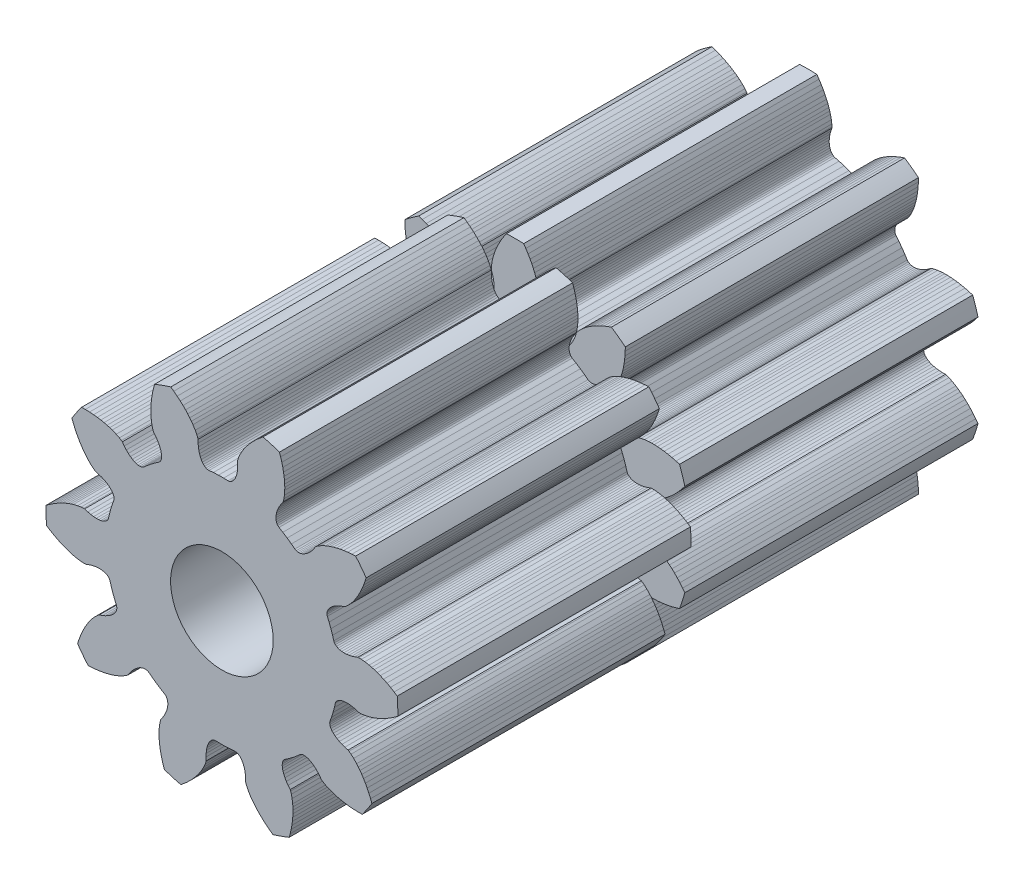
SolidWorks part; units mm, degrees
ref_plane "Front Plane" through (0, 0, 0) normal (0, 0, 1) x (1, 0, 0)
ref_plane "Top Plane" through (0, 0, 0) normal (0, 1, 0) x (1, 0, 0)
ref_plane "Right Plane" through (0, 0, 0) normal (1, 0, 0) x (0, 0, -1)
sketch "Sketch1" plane through (0, 0, 0) normal (0, 0, 1) x (1, 0, 0)
  line L0 (11.2428, -4.5485) -> (11.2517, -4.4039)
  line L1 (11.2517, -4.4039) -> (11.266, -4.2669)
  line L2 (11.266, -4.2669) -> (11.2847, -4.1393)
  line L3 (11.2847, -4.1393) -> (11.3071, -4.0209)
  line L4 (11.3071, -4.0209) -> (11.3325, -3.912)
  line L5 (11.3325, -3.912) -> (11.3608, -3.8103)
  line L6 (11.3608, -3.8103) -> (11.3897, -3.7211)
  line L7 (11.3897, -3.7211) -> (11.4208, -3.6371)
  line L8 (11.4208, -3.6371) -> (11.4807, -3.5016)
  line L9 (11.4807, -3.5016) -> (11.5377, -3.3971)
  line L10 (11.5377, -3.3971) -> (11.5845, -3.3262)
  line L11 (11.5845, -3.3262) -> (11.6076, -3.2964)
  line L12 (11.6076, -3.2964) -> (11.7007, -3.2317)
  line L13 (11.7007, -3.2317) -> (11.7827, -3.1653)
  line L14 (11.7827, -3.1653) -> (11.8533, -3.098)
  line L15 (11.8533, -3.098) -> (11.9128, -3.0308)
  line L16 (11.9128, -3.0308) -> (11.9612, -2.9643)
  line L17 (11.9612, -2.9643) -> (11.9989, -2.8995)
  line L18 (11.9989, -2.8995) -> (12.0259, -2.837)
  line L19 (12.0259, -2.837) -> (12.0426, -2.7776)
  line L20 (12.0426, -2.7776) -> (12.0493, -2.7222)
  line L21 (12.0493, -2.7222) -> (12.0463, -2.6714)
  line L22 (12.0463, -2.6714) -> (12.0342, -2.6259)
  line L23 (12.0342, -2.6259) -> (12.0067, -2.5776)
  line L24 (12.0067, -2.5776) -> (11.9109, -2.4617)
  line L25 (11.9109, -2.4617) -> (11.8044, -2.3217)
  line L26 (11.8044, -2.3217) -> (11.7041, -2.1772)
  line L27 (11.7041, -2.1772) -> (11.6236, -2.0503)
  line L28 (11.6236, -2.0503) -> (11.5861, -2.0092)
  line L29 (11.5861, -2.0092) -> (11.5466, -1.9836)
  line L30 (11.5466, -1.9836) -> (11.4992, -1.9651)
  line L31 (11.4992, -1.9651) -> (11.4444, -1.9543)
  line L32 (11.4444, -1.9543) -> (11.3828, -1.9518)
  line L33 (11.3828, -1.9518) -> (11.315, -1.9582)
  line L34 (11.315, -1.9582) -> (11.2417, -1.974)
  line L35 (11.2417, -1.974) -> (11.1635, -1.9995)
  line L36 (11.1635, -1.9995) -> (11.0812, -2.0353)
  line L37 (11.0812, -2.0353) -> (10.9954, -2.0817)
  line L38 (10.9954, -2.0817) -> (10.907, -2.1391)
  line L39 (10.907, -2.1391) -> (10.8166, -2.2077)
  line L40 (10.8166, -2.2077) -> (10.7811, -2.2204)
  line L41 (10.7811, -2.2204) -> (10.6992, -2.243)
  line L42 (10.6992, -2.243) -> (10.5823, -2.2649)
  line L43 (10.5823, -2.2649) -> (10.4348, -2.2801)
  line L44 (10.4348, -2.2801) -> (10.3453, -2.2837)
  line L45 (10.3453, -2.2837) -> (10.2516, -2.2836)
  line L46 (10.2516, -2.2836) -> (10.1461, -2.2791)
  line L47 (10.1461, -2.2791) -> (10.0348, -2.2696)
  line L48 (10.0348, -2.2696) -> (9.9151, -2.2543)
  line L49 (9.9151, -2.2543) -> (9.7881, -2.2327)
  line L50 (9.7881, -2.2327) -> (9.6533, -2.2039)
  line L51 (9.6533, -2.2039) -> (9.5131, -2.1677)
  line L52 (9.5131, -2.1677) -> (9.3912, -2.1311)
  line L53 (9.2098, -1.5726) -> (9.2868, -1.4714)
  line L54 (9.2868, -1.4714) -> (9.379, -1.3597)
  line L55 (9.379, -1.3597) -> (9.4711, -1.2572)
  line L56 (9.4711, -1.2572) -> (9.5612, -1.165)
  line L57 (9.5612, -1.165) -> (9.649, -1.0823)
  line L58 (9.649, -1.0823) -> (9.7335, -1.0092)
  line L59 (9.7335, -1.0092) -> (9.8162, -0.9435)
  line L60 (9.8162, -0.9435) -> (9.8919, -0.8883)
  line L61 (9.8919, -0.8883) -> (9.9665, -0.8387)
  line L62 (9.9665, -0.8387) -> (10.0947, -0.7642)
  line L63 (10.0947, -0.7642) -> (10.2021, -0.7133)
  line L64 (10.2021, -0.7133) -> (10.2817, -0.6834)
  line L65 (10.2817, -0.6834) -> (10.3179, -0.6728)
  line L66 (10.3179, -0.6728) -> (10.4313, -0.6752)
  line L67 (10.4313, -0.6752) -> (10.5366, -0.6696)
  line L68 (10.5366, -0.6696) -> (10.6333, -0.6568)
  line L69 (10.6333, -0.6568) -> (10.7209, -0.6373)
  line L70 (10.7209, -0.6373) -> (10.7992, -0.612)
  line L71 (10.7992, -0.612) -> (10.8678, -0.5817)
  line L72 (10.8678, -0.5817) -> (10.9263, -0.547)
  line L73 (10.9263, -0.547) -> (10.9747, -0.5088)
  line L74 (10.9747, -0.5088) -> (11.0127, -0.4679)
  line L75 (11.0127, -0.4679) -> (11.0402, -0.4251)
  line L76 (11.0402, -0.4251) -> (11.0571, -0.3811)
  line L77 (11.0571, -0.3811) -> (11.0633, -0.3259)
  line L78 (11.0633, -0.3259) -> (11.0539, -0.1759)
  line L79 (11.0539, -0.1759) -> (11.05, 0)
  line L80 (11.05, 0) -> (11.0539, 0.1759)
  line L81 (11.0539, 0.1759) -> (11.0633, 0.3259)
  line L82 (11.0633, 0.3259) -> (11.0571, 0.3812)
  line L83 (11.0571, 0.3812) -> (11.0402, 0.4251)
  line L84 (11.0402, 0.4251) -> (11.0127, 0.468)
  line L85 (11.0127, 0.468) -> (10.9747, 0.5089)
  line L86 (10.9747, 0.5089) -> (10.9263, 0.5471)
  line L87 (10.9263, 0.5471) -> (10.8678, 0.5817)
  line L88 (10.8678, 0.5817) -> (10.7992, 0.6121)
  line L89 (10.7992, 0.6121) -> (10.7209, 0.6374)
  line L90 (10.7209, 0.6374) -> (10.6333, 0.6568)
  line L91 (10.6333, 0.6568) -> (10.5366, 0.6697)
  line L92 (10.5366, 0.6697) -> (10.4313, 0.6753)
  line L93 (10.4313, 0.6753) -> (10.3179, 0.6729)
  line L94 (10.3179, 0.6729) -> (10.2817, 0.6834)
  line L95 (10.2817, 0.6834) -> (10.2021, 0.7133)
  line L96 (10.2021, 0.7133) -> (10.0947, 0.7643)
  line L97 (10.0947, 0.7643) -> (9.9665, 0.8387)
  line L98 (9.9665, 0.8387) -> (9.8919, 0.8884)
  line L99 (9.8919, 0.8884) -> (9.8162, 0.9436)
  line L100 (9.8162, 0.9436) -> (9.7335, 1.0093)
  line L101 (9.7335, 1.0093) -> (9.649, 1.0824)
  line L102 (9.649, 1.0824) -> (9.5612, 1.165)
  line L103 (9.5612, 1.165) -> (9.4711, 1.2572)
  line L104 (9.4711, 1.2572) -> (9.379, 1.3597)
  line L105 (9.379, 1.3597) -> (9.2868, 1.4714)
  line L106 (9.2868, 1.4714) -> (9.2098, 1.5727)
  line L107 (9.3912, 2.1311) -> (9.5131, 2.1677)
  line L108 (9.5131, 2.1677) -> (9.6533, 2.2039)
  line L109 (9.6533, 2.2039) -> (9.788, 2.2327)
  line L110 (9.788, 2.2327) -> (9.9151, 2.2544)
  line L111 (9.9151, 2.2544) -> (10.0347, 2.2696)
  line L112 (10.0347, 2.2696) -> (10.1461, 2.2791)
  line L113 (10.1461, 2.2791) -> (10.2516, 2.2836)
  line L114 (10.2516, 2.2836) -> (10.3453, 2.2837)
  line L115 (10.3453, 2.2837) -> (10.4348, 2.2801)
  line L116 (10.4348, 2.2801) -> (10.5823, 2.265)
  line L117 (10.5823, 2.265) -> (10.6992, 2.2431)
  line L118 (10.6992, 2.2431) -> (10.7811, 2.2205)
  line L119 (10.7811, 2.2205) -> (10.8166, 2.2078)
  line L120 (10.8166, 2.2078) -> (10.9069, 2.1391)
  line L121 (10.9069, 2.1391) -> (10.9954, 2.0818)
  line L122 (10.9954, 2.0818) -> (11.0812, 2.0353)
  line L123 (11.0812, 2.0353) -> (11.1635, 1.9995)
  line L124 (11.1635, 1.9995) -> (11.2417, 1.974)
  line L125 (11.2417, 1.974) -> (11.315, 1.9583)
  line L126 (11.315, 1.9583) -> (11.3828, 1.9519)
  line L127 (11.3828, 1.9519) -> (11.4444, 1.9543)
  line L128 (11.4444, 1.9543) -> (11.4991, 1.9651)
  line L129 (11.4991, 1.9651) -> (11.5465, 1.9836)
  line L130 (11.5465, 1.9836) -> (11.586, 2.0092)
  line L131 (11.586, 2.0092) -> (11.6235, 2.0503)
  line L132 (11.6235, 2.0503) -> (11.7041, 2.1772)
  line L133 (11.7041, 2.1772) -> (11.8043, 2.3218)
  line L134 (11.8043, 2.3218) -> (11.9109, 2.4618)
  line L135 (11.9109, 2.4618) -> (12.0067, 2.5776)
  line L136 (12.0067, 2.5776) -> (12.0341, 2.626)
  line L137 (12.0341, 2.626) -> (12.0463, 2.6715)
  line L138 (12.0463, 2.6715) -> (12.0492, 2.7223)
  line L139 (12.0492, 2.7223) -> (12.0426, 2.7777)
  line L140 (12.0426, 2.7777) -> (12.0259, 2.837)
  line L141 (12.0259, 2.837) -> (11.9988, 2.8995)
  line L142 (11.9988, 2.8995) -> (11.9612, 2.9643)
  line L143 (11.9612, 2.9643) -> (11.9128, 3.0308)
  line L144 (11.9128, 3.0308) -> (11.8533, 3.0981)
  line L145 (11.8533, 3.0981) -> (11.7826, 3.1653)
  line L146 (11.7826, 3.1653) -> (11.7007, 3.2317)
  line L147 (11.7007, 3.2317) -> (11.6075, 3.2964)
  line L148 (11.6075, 3.2964) -> (11.5845, 3.3262)
  line L149 (11.5845, 3.3262) -> (11.5377, 3.3972)
  line L150 (11.5377, 3.3972) -> (11.4807, 3.5016)
  line L151 (11.4807, 3.5016) -> (11.4208, 3.6372)
  line L152 (11.4208, 3.6372) -> (11.3896, 3.7212)
  line L153 (11.3896, 3.7212) -> (11.3608, 3.8103)
  line L154 (11.3608, 3.8103) -> (11.3325, 3.9121)
  line L155 (11.3325, 3.9121) -> (11.3071, 4.0209)
  line L156 (11.3071, 4.0209) -> (11.2846, 4.1394)
  line L157 (11.2846, 4.1394) -> (11.2659, 4.2669)
  line L158 (11.2659, 4.2669) -> (11.2517, 4.404)
  line L159 (11.2517, 4.404) -> (11.2428, 4.5485)
  line L160 (11.2428, 4.5485) -> (11.2399, 4.6757)
  line L161 (11.715, 5.0209) -> (11.8351, 4.9789)
  line L162 (11.8351, 4.9789) -> (11.9698, 4.9257)
  line L163 (11.9698, 4.9257) -> (12.0958, 4.8698)
  line L164 (12.0958, 4.8698) -> (12.2113, 4.8127)
  line L165 (12.2113, 4.8127) -> (12.3171, 4.7547)
  line L166 (12.3171, 4.7547) -> (12.4127, 4.6969)
  line L167 (12.4127, 4.6969) -> (12.5007, 4.6385)
  line L168 (12.5007, 4.6385) -> (12.5766, 4.5836)
  line L169 (12.5766, 4.5836) -> (12.6469, 4.528)
  line L170 (12.6469, 4.528) -> (12.7573, 4.4291)
  line L171 (12.7573, 4.4291) -> (12.839, 4.3427)
  line L172 (12.839, 4.3427) -> (12.892, 4.2762)
  line L173 (12.892, 4.2762) -> (12.9132, 4.2451)
  line L174 (12.9132, 4.2451) -> (12.946, 4.1364)
  line L175 (12.946, 4.1364) -> (12.9838, 4.038)
  line L176 (12.9838, 4.038) -> (13.0259, 3.9501)
  line L177 (13.0259, 3.9501) -> (13.0715, 3.8727)
  line L178 (13.0715, 3.8727) -> (13.1197, 3.8061)
  line L179 (13.1197, 3.8061) -> (13.1698, 3.7503)
  line L180 (13.1698, 3.7503) -> (13.2209, 3.7053)
  line L181 (13.2209, 3.7053) -> (13.2721, 3.671)
  line L182 (13.2721, 3.671) -> (13.3228, 3.6476)
  line L183 (13.3228, 3.6476) -> (13.372, 3.6347)
  line L184 (13.372, 3.6347) -> (13.419, 3.6322)
  line L185 (13.419, 3.6322) -> (13.4735, 3.6434)
  line L186 (13.4735, 3.6434) -> (13.6133, 3.6987)
  line L187 (13.6133, 3.6987) -> (13.7794, 3.7567)
  line L188 (13.7794, 3.7567) -> (13.9478, 3.8074)
  line L189 (13.9478, 3.8074) -> (14.0934, 3.8448)
  line L190 (14.0934, 3.8448) -> (14.1441, 3.8678)
  line L191 (14.1441, 3.8678) -> (14.1806, 3.8974)
  line L192 (14.1806, 3.8974) -> (14.2129, 3.9368)
  line L193 (14.2129, 3.9368) -> (14.2401, 3.9855)
  line L194 (14.2401, 3.9855) -> (14.2614, 4.0434)
  line L195 (14.2614, 4.0434) -> (14.2763, 4.1098)
  line L196 (14.2763, 4.1098) -> (14.284, 4.1844)
  line L197 (14.284, 4.1844) -> (14.2838, 4.2666)
  line L198 (14.2838, 4.2666) -> (14.2752, 4.356)
  line L199 (14.2752, 4.356) -> (14.2576, 4.4519)
  line L200 (14.2576, 4.4519) -> (14.2304, 4.5538)
  line L201 (14.2304, 4.5538) -> (14.193, 4.6609)
  line L202 (14.193, 4.6609) -> (14.1919, 4.6986)
  line L203 (14.1919, 4.6986) -> (14.1957, 4.7835)
  line L204 (14.1957, 4.7835) -> (14.211, 4.9014)
  line L205 (14.211, 4.9014) -> (14.2422, 5.0463)
  line L206 (14.2422, 5.0463) -> (14.2664, 5.1326)
  line L207 (14.2664, 5.1326) -> (14.2955, 5.2217)
  line L208 (14.2955, 5.2217) -> (14.3324, 5.3207)
  line L209 (14.3324, 5.3207) -> (14.3758, 5.4236)
  line L210 (14.3758, 5.4236) -> (14.4273, 5.5327)
  line L211 (14.4273, 5.5327) -> (14.4871, 5.6468)
  line L212 (14.4871, 5.6468) -> (14.5562, 5.7661)
  line L213 (14.5562, 5.7661) -> (14.6339, 5.8883)
  line L214 (14.6339, 5.8883) -> (14.7064, 5.9928)
  line L215 (15.2936, 5.9928) -> (15.3661, 5.8883)
  line L216 (15.3661, 5.8883) -> (15.4438, 5.7661)
  line L217 (15.4438, 5.7661) -> (15.5128, 5.6468)
  line L218 (15.5128, 5.6468) -> (15.5727, 5.5327)
  line L219 (15.5727, 5.5327) -> (15.6242, 5.4236)
  line L220 (15.6242, 5.4236) -> (15.6676, 5.3207)
  line L221 (15.6676, 5.3207) -> (15.7045, 5.2217)
  line L222 (15.7045, 5.2217) -> (15.7336, 5.1326)
  line L223 (15.7336, 5.1326) -> (15.7578, 5.0464)
  line L224 (15.7578, 5.0464) -> (15.7889, 4.9014)
  line L225 (15.7889, 4.9014) -> (15.8042, 4.7835)
  line L226 (15.8042, 4.7835) -> (15.8081, 4.6986)
  line L227 (15.8081, 4.6986) -> (15.8069, 4.6609)
  line L228 (15.8069, 4.6609) -> (15.7696, 4.5538)
  line L229 (15.7696, 4.5538) -> (15.7424, 4.4519)
  line L230 (15.7424, 4.4519) -> (15.7247, 4.356)
  line L231 (15.7247, 4.356) -> (15.7161, 4.2666)
  line L232 (15.7161, 4.2666) -> (15.716, 4.1844)
  line L233 (15.716, 4.1844) -> (15.7237, 4.1098)
  line L234 (15.7237, 4.1098) -> (15.7385, 4.0434)
  line L235 (15.7385, 4.0434) -> (15.7599, 3.9855)
  line L236 (15.7599, 3.9855) -> (15.7871, 3.9368)
  line L237 (15.7871, 3.9368) -> (15.8193, 3.8974)
  line L238 (15.8193, 3.8974) -> (15.8559, 3.8678)
  line L239 (15.8559, 3.8678) -> (15.9065, 3.8448)
  line L240 (15.9065, 3.8448) -> (16.0521, 3.8074)
  line L241 (16.0521, 3.8074) -> (16.2206, 3.7567)
  line L242 (16.2206, 3.7567) -> (16.3867, 3.6987)
  line L243 (16.3867, 3.6987) -> (16.5264, 3.6434)
  line L244 (16.5264, 3.6434) -> (16.5809, 3.6322)
  line L245 (16.5809, 3.6322) -> (16.6279, 3.6347)
  line L246 (16.6279, 3.6347) -> (16.6772, 3.6476)
  line L247 (16.6772, 3.6476) -> (16.7278, 3.6711)
  line L248 (16.7278, 3.6711) -> (16.7791, 3.7053)
  line L249 (16.7791, 3.7053) -> (16.8301, 3.7503)
  line L250 (16.8301, 3.7503) -> (16.8802, 3.8061)
  line L251 (16.8802, 3.8061) -> (16.9284, 3.8727)
  line L252 (16.9284, 3.8727) -> (16.974, 3.9501)
  line L253 (16.974, 3.9501) -> (17.0161, 4.038)
  line L254 (17.0161, 4.038) -> (17.054, 4.1365)
  line L255 (17.054, 4.1365) -> (17.0867, 4.2451)
  line L256 (17.0867, 4.2451) -> (17.108, 4.2762)
  line L257 (17.108, 4.2762) -> (17.161, 4.3427)
  line L258 (17.161, 4.3427) -> (17.2427, 4.4291)
  line L259 (17.2427, 4.4291) -> (17.3531, 4.528)
  line L260 (17.3531, 4.528) -> (17.4233, 4.5836)
  line L261 (17.4233, 4.5836) -> (17.4992, 4.6385)
  line L262 (17.4992, 4.6385) -> (17.5873, 4.6969)
  line L263 (17.5873, 4.6969) -> (17.6829, 4.7547)
  line L264 (17.6829, 4.7547) -> (17.7886, 4.8127)
  line L265 (17.7886, 4.8127) -> (17.9042, 4.8699)
  line L266 (17.9042, 4.8699) -> (18.0301, 4.9258)
  line L267 (18.0301, 4.9258) -> (18.1648, 4.9789)
  line L268 (18.1648, 4.9789) -> (18.2849, 5.0209)
  line L269 (18.76, 4.6758) -> (18.7572, 4.5486)
  line L270 (18.7572, 4.5486) -> (18.7483, 4.404)
  line L271 (18.7483, 4.404) -> (18.734, 4.2669)
  line L272 (18.734, 4.2669) -> (18.7153, 4.1394)
  line L273 (18.7153, 4.1394) -> (18.6928, 4.0209)
  line L274 (18.6928, 4.0209) -> (18.6675, 3.9121)
  line L275 (18.6675, 3.9121) -> (18.6392, 3.8103)
  line L276 (18.6392, 3.8103) -> (18.6103, 3.7212)
  line L277 (18.6103, 3.7212) -> (18.5792, 3.6372)
  line L278 (18.5792, 3.6372) -> (18.5192, 3.5016)
  line L279 (18.5192, 3.5016) -> (18.4623, 3.3972)
  line L280 (18.4623, 3.3972) -> (18.4155, 3.3263)
  line L281 (18.4155, 3.3263) -> (18.3924, 3.2965)
  line L282 (18.3924, 3.2965) -> (18.2992, 3.2317)
  line L283 (18.2992, 3.2317) -> (18.2173, 3.1653)
  line L284 (18.2173, 3.1653) -> (18.1467, 3.0981)
  line L285 (18.1467, 3.0981) -> (18.0872, 3.0308)
  line L286 (18.0872, 3.0308) -> (18.0387, 2.9644)
  line L287 (18.0387, 2.9644) -> (18.0011, 2.8995)
  line L288 (18.0011, 2.8995) -> (17.9741, 2.837)
  line L289 (17.9741, 2.837) -> (17.9574, 2.7777)
  line L290 (17.9574, 2.7777) -> (17.9507, 2.7223)
  line L291 (17.9507, 2.7223) -> (17.9537, 2.6715)
  line L292 (17.9537, 2.6715) -> (17.9658, 2.626)
  line L293 (17.9658, 2.626) -> (17.9933, 2.5777)
  line L294 (17.9933, 2.5777) -> (18.0891, 2.4618)
  line L295 (18.0891, 2.4618) -> (18.1956, 2.3218)
  line L296 (18.1956, 2.3218) -> (18.2959, 2.1772)
  line L297 (18.2959, 2.1772) -> (18.3764, 2.0503)
  line L298 (18.3764, 2.0503) -> (18.4139, 2.0093)
  line L299 (18.4139, 2.0093) -> (18.4534, 1.9836)
  line L300 (18.4534, 1.9836) -> (18.5008, 1.9651)
  line L301 (18.5008, 1.9651) -> (18.5556, 1.9544)
  line L302 (18.5556, 1.9544) -> (18.6172, 1.9519)
  line L303 (18.6172, 1.9519) -> (18.6849, 1.9583)
  line L304 (18.6849, 1.9583) -> (18.7583, 1.974)
  line L305 (18.7583, 1.974) -> (18.8364, 1.9996)
  line L306 (18.8364, 1.9996) -> (18.9188, 2.0354)
  line L307 (18.9188, 2.0354) -> (19.0046, 2.0818)
  line L308 (19.0046, 2.0818) -> (19.093, 2.1392)
  line L309 (19.093, 2.1392) -> (19.1834, 2.2078)
  line L310 (19.1834, 2.2078) -> (19.2188, 2.2205)
  line L311 (19.2188, 2.2205) -> (19.3008, 2.2431)
  line L312 (19.3008, 2.2431) -> (19.4177, 2.265)
  line L313 (19.4177, 2.265) -> (19.5651, 2.2801)
  line L314 (19.5651, 2.2801) -> (19.6547, 2.2838)
  line L315 (19.6547, 2.2838) -> (19.7484, 2.2837)
  line L316 (19.7484, 2.2837) -> (19.8539, 2.2791)
  line L317 (19.8539, 2.2791) -> (19.9652, 2.2696)
  line L318 (19.9652, 2.2696) -> (20.0848, 2.2544)
  line L319 (20.0848, 2.2544) -> (20.2119, 2.2328)
  line L320 (20.2119, 2.2328) -> (20.3467, 2.204)
  line L321 (20.3467, 2.204) -> (20.4869, 2.1678)
  line L322 (20.4869, 2.1678) -> (20.6088, 2.1312)
  line L323 (20.7902, 1.5727) -> (20.7132, 1.4714)
  line L324 (20.7132, 1.4714) -> (20.621, 1.3598)
  line L325 (20.621, 1.3598) -> (20.5289, 1.2572)
  line L326 (20.5289, 1.2572) -> (20.4388, 1.165)
  line L327 (20.4388, 1.165) -> (20.351, 1.0824)
  line L328 (20.351, 1.0824) -> (20.2665, 1.0093)
  line L329 (20.2665, 1.0093) -> (20.1838, 0.9436)
  line L330 (20.1838, 0.9436) -> (20.108, 0.8884)
  line L331 (20.108, 0.8884) -> (20.0335, 0.8388)
  line L332 (20.0335, 0.8388) -> (19.9053, 0.7643)
  line L333 (19.9053, 0.7643) -> (19.7979, 0.7133)
  line L334 (19.7979, 0.7133) -> (19.7183, 0.6834)
  line L335 (19.7183, 0.6834) -> (19.6821, 0.6729)
  line L336 (19.6821, 0.6729) -> (19.5687, 0.6753)
  line L337 (19.5687, 0.6753) -> (19.4634, 0.6697)
  line L338 (19.4634, 0.6697) -> (19.3667, 0.6568)
  line L339 (19.3667, 0.6568) -> (19.279, 0.6374)
  line L340 (19.279, 0.6374) -> (19.2008, 0.6121)
  line L341 (19.2008, 0.6121) -> (19.1322, 0.5818)
  line L342 (19.1322, 0.5818) -> (19.0736, 0.5471)
  line L343 (19.0736, 0.5471) -> (19.0253, 0.5089)
  line L344 (19.0253, 0.5089) -> (18.9873, 0.468)
  line L345 (18.9873, 0.468) -> (18.9598, 0.4252)
  line L346 (18.9598, 0.4252) -> (18.9429, 0.3812)
  line L347 (18.9429, 0.3812) -> (18.9367, 0.3259)
  line L348 (18.9367, 0.3259) -> (18.9461, 0.1759)
  line L349 (18.9461, 0.1759) -> (18.95, 0)
  line L350 (18.95, 0) -> (18.9461, -0.1758)
  line L351 (18.9461, -0.1758) -> (18.9367, -0.3259)
  line L352 (18.9367, -0.3259) -> (18.9429, -0.3811)
  line L353 (18.9429, -0.3811) -> (18.9598, -0.4251)
  line L354 (18.9598, -0.4251) -> (18.9873, -0.4679)
  line L355 (18.9873, -0.4679) -> (19.0253, -0.5088)
  line L356 (19.0253, -0.5088) -> (19.0736, -0.547)
  line L357 (19.0736, -0.547) -> (19.1322, -0.5817)
  line L358 (19.1322, -0.5817) -> (19.2008, -0.612)
  line L359 (19.2008, -0.612) -> (19.279, -0.6373)
  line L360 (19.279, -0.6373) -> (19.3667, -0.6567)
  line L361 (19.3667, -0.6567) -> (19.4634, -0.6696)
  line L362 (19.4634, -0.6696) -> (19.5687, -0.6752)
  line L363 (19.5687, -0.6752) -> (19.6821, -0.6728)
  line L364 (19.6821, -0.6728) -> (19.7183, -0.6834)
  line L365 (19.7183, -0.6834) -> (19.7979, -0.7132)
  line L366 (19.7979, -0.7132) -> (19.9053, -0.7642)
  line L367 (19.9053, -0.7642) -> (20.0335, -0.8387)
  line L368 (20.0335, -0.8387) -> (20.108, -0.8883)
  line L369 (20.108, -0.8883) -> (20.1838, -0.9435)
  line L370 (20.1838, -0.9435) -> (20.2665, -1.0092)
  line L371 (20.2665, -1.0092) -> (20.351, -1.0823)
  line L372 (20.351, -1.0823) -> (20.4388, -1.1649)
  line L373 (20.4388, -1.1649) -> (20.5289, -1.2571)
  line L374 (20.5289, -1.2571) -> (20.621, -1.3597)
  line L375 (20.621, -1.3597) -> (20.7132, -1.4714)
  line L376 (20.7132, -1.4714) -> (20.7902, -1.5726)
  line L377 (20.6088, -2.131) -> (20.4869, -2.1677)
  line L378 (20.4869, -2.1677) -> (20.3467, -2.2039)
  line L379 (20.3467, -2.2039) -> (20.2119, -2.2327)
  line L380 (20.2119, -2.2327) -> (20.0849, -2.2543)
  line L381 (20.0849, -2.2543) -> (19.9652, -2.2695)
  line L382 (19.9652, -2.2695) -> (19.8539, -2.279)
  line L383 (19.8539, -2.279) -> (19.7484, -2.2836)
  line L384 (19.7484, -2.2836) -> (19.6547, -2.2837)
  line L385 (19.6547, -2.2837) -> (19.5652, -2.28)
  line L386 (19.5652, -2.28) -> (19.4177, -2.2649)
  line L387 (19.4177, -2.2649) -> (19.3008, -2.243)
  line L388 (19.3008, -2.243) -> (19.2189, -2.2204)
  line L389 (19.2189, -2.2204) -> (19.1834, -2.2077)
  line L390 (19.1834, -2.2077) -> (19.093, -2.1391)
  line L391 (19.093, -2.1391) -> (19.0046, -2.0817)
  line L392 (19.0046, -2.0817) -> (18.9188, -2.0353)
  line L393 (18.9188, -2.0353) -> (18.8365, -1.9995)
  line L394 (18.8365, -1.9995) -> (18.7583, -1.9739)
  line L395 (18.7583, -1.9739) -> (18.685, -1.9582)
  line L396 (18.685, -1.9582) -> (18.6172, -1.9518)
  line L397 (18.6172, -1.9518) -> (18.5556, -1.9543)
  line L398 (18.5556, -1.9543) -> (18.5008, -1.965)
  line L399 (18.5008, -1.965) -> (18.4534, -1.9835)
  line L400 (18.4534, -1.9835) -> (18.4139, -2.0092)
  line L401 (18.4139, -2.0092) -> (18.3764, -2.0502)
  line L402 (18.3764, -2.0502) -> (18.2959, -2.1771)
  line L403 (18.2959, -2.1771) -> (18.1956, -2.3217)
  line L404 (18.1956, -2.3217) -> (18.0891, -2.4617)
  line L405 (18.0891, -2.4617) -> (17.9933, -2.5776)
  line L406 (17.9933, -2.5776) -> (17.9658, -2.6259)
  line L407 (17.9658, -2.6259) -> (17.9537, -2.6714)
  line L408 (17.9537, -2.6714) -> (17.9507, -2.7222)
  line L409 (17.9507, -2.7222) -> (17.9574, -2.7776)
  line L410 (17.9574, -2.7776) -> (17.9741, -2.8369)
  line L411 (17.9741, -2.8369) -> (18.0011, -2.8994)
  line L412 (18.0011, -2.8994) -> (18.0387, -2.9643)
  line L413 (18.0387, -2.9643) -> (18.0872, -3.0307)
  line L414 (18.0872, -3.0307) -> (18.1467, -3.098)
  line L415 (18.1467, -3.098) -> (18.2173, -3.1652)
  line L416 (18.2173, -3.1652) -> (18.2992, -3.2316)
  line L417 (18.2992, -3.2316) -> (18.3924, -3.2964)
  line L418 (18.3924, -3.2964) -> (18.4155, -3.3262)
  line L419 (18.4155, -3.3262) -> (18.4623, -3.3971)
  line L420 (18.4623, -3.3971) -> (18.5193, -3.5015)
  line L421 (18.5193, -3.5015) -> (18.5792, -3.6371)
  line L422 (18.5792, -3.6371) -> (18.6103, -3.7211)
  line L423 (18.6103, -3.7211) -> (18.6392, -3.8102)
  line L424 (18.6392, -3.8102) -> (18.6675, -3.912)
  line L425 (18.6675, -3.912) -> (18.6929, -4.0208)
  line L426 (18.6929, -4.0208) -> (18.7153, -4.1393)
  line L427 (18.7153, -4.1393) -> (18.734, -4.2668)
  line L428 (18.734, -4.2668) -> (18.7483, -4.4039)
  line L429 (18.7483, -4.4039) -> (18.7572, -4.5484)
  line L430 (18.7572, -4.5484) -> (18.76, -4.6757)
  line L431 (18.285, -5.0208) -> (18.1648, -4.9788)
  line L432 (18.1648, -4.9788) -> (18.0301, -4.9257)
  line L433 (18.0301, -4.9257) -> (17.9042, -4.8698)
  line L434 (17.9042, -4.8698) -> (17.7886, -4.8126)
  line L435 (17.7886, -4.8126) -> (17.6829, -4.7546)
  line L436 (17.6829, -4.7546) -> (17.5873, -4.6968)
  line L437 (17.5873, -4.6968) -> (17.4992, -4.6385)
  line L438 (17.4992, -4.6385) -> (17.4234, -4.5835)
  line L439 (17.4234, -4.5835) -> (17.3531, -4.5279)
  line L440 (17.3531, -4.5279) -> (17.2427, -4.429)
  line L441 (17.2427, -4.429) -> (17.161, -4.3426)
  line L442 (17.161, -4.3426) -> (17.108, -4.2761)
  line L443 (17.108, -4.2761) -> (17.0868, -4.245)
  line L444 (17.0868, -4.245) -> (17.054, -4.1364)
  line L445 (17.054, -4.1364) -> (17.0161, -4.038)
  line L446 (17.0161, -4.038) -> (16.974, -3.95)
  line L447 (16.974, -3.95) -> (16.9284, -3.8726)
  line L448 (16.9284, -3.8726) -> (16.8802, -3.806)
  line L449 (16.8802, -3.806) -> (16.8302, -3.7502)
  line L450 (16.8302, -3.7502) -> (16.7791, -3.7052)
  line L451 (16.7791, -3.7052) -> (16.7278, -3.671)
  line L452 (16.7278, -3.671) -> (16.6772, -3.6475)
  line L453 (16.6772, -3.6475) -> (16.6279, -3.6346)
  line L454 (16.6279, -3.6346) -> (16.5809, -3.6321)
  line L455 (16.5809, -3.6321) -> (16.5265, -3.6433)
  line L456 (16.5265, -3.6433) -> (16.3867, -3.6986)
  line L457 (16.3867, -3.6986) -> (16.2206, -3.7567)
  line L458 (16.2206, -3.7567) -> (16.0521, -3.8073)
  line L459 (16.0521, -3.8073) -> (15.9066, -3.8447)
  line L460 (15.9066, -3.8447) -> (15.8559, -3.8677)
  line L461 (15.8559, -3.8677) -> (15.8193, -3.8973)
  line L462 (15.8193, -3.8973) -> (15.7871, -3.9367)
  line L463 (15.7871, -3.9367) -> (15.7599, -3.9855)
  line L464 (15.7599, -3.9855) -> (15.7385, -4.0433)
  line L465 (15.7385, -4.0433) -> (15.7237, -4.1097)
  line L466 (15.7237, -4.1097) -> (15.716, -4.1843)
  line L467 (15.716, -4.1843) -> (15.7161, -4.2665)
  line L468 (15.7161, -4.2665) -> (15.7247, -4.3559)
  line L469 (15.7247, -4.3559) -> (15.7424, -4.4518)
  line L470 (15.7424, -4.4518) -> (15.7696, -4.5537)
  line L471 (15.7696, -4.5537) -> (15.8069, -4.6609)
  line L472 (15.8069, -4.6609) -> (15.8081, -4.6985)
  line L473 (15.8081, -4.6985) -> (15.8042, -4.7834)
  line L474 (15.8042, -4.7834) -> (15.789, -4.9014)
  line L475 (15.789, -4.9014) -> (15.7578, -5.0463)
  line L476 (15.7578, -5.0463) -> (15.7336, -5.1325)
  line L477 (15.7336, -5.1325) -> (15.7045, -5.2216)
  line L478 (15.7045, -5.2216) -> (15.6676, -5.3206)
  line L479 (15.6676, -5.3206) -> (15.6242, -5.4235)
  line L480 (15.6242, -5.4235) -> (15.5727, -5.5326)
  line L481 (15.5727, -5.5326) -> (15.5129, -5.6468)
  line L482 (15.5129, -5.6468) -> (15.4438, -5.766)
  line L483 (15.4438, -5.766) -> (15.3661, -5.8882)
  line L484 (15.3661, -5.8882) -> (15.2936, -5.9928)
  line L485 (14.7064, -5.9928) -> (14.6339, -5.8882)
  line L486 (14.6339, -5.8882) -> (14.5561, -5.766)
  line L487 (14.5561, -5.766) -> (14.4871, -5.6468)
  line L488 (14.4871, -5.6468) -> (14.4272, -5.5326)
  line L489 (14.4272, -5.5326) -> (14.3758, -5.4235)
  line L490 (14.3758, -5.4235) -> (14.3324, -5.3206)
  line L491 (14.3324, -5.3206) -> (14.2954, -5.2216)
  line L492 (14.2954, -5.2216) -> (14.2664, -5.1325)
  line L493 (14.2664, -5.1325) -> (14.2422, -5.0463)
  line L494 (14.2422, -5.0463) -> (14.211, -4.9014)
  line L495 (14.211, -4.9014) -> (14.1957, -4.7834)
  line L496 (14.1957, -4.7834) -> (14.1919, -4.6985)
  line L497 (14.1919, -4.6985) -> (14.193, -4.6608)
  line L498 (14.193, -4.6608) -> (14.2304, -4.5537)
  line L499 (14.2304, -4.5537) -> (14.2576, -4.4518)
  line L500 (14.2576, -4.4518) -> (14.2752, -4.3559)
  line L501 (14.2752, -4.3559) -> (14.2838, -4.2665)
  line L502 (14.2838, -4.2665) -> (14.284, -4.1843)
  line L503 (14.284, -4.1843) -> (14.2763, -4.1097)
  line L504 (14.2763, -4.1097) -> (14.2614, -4.0433)
  line L505 (14.2614, -4.0433) -> (14.24, -3.9855)
  line L506 (14.24, -3.9855) -> (14.2129, -3.9367)
  line L507 (14.2129, -3.9367) -> (14.1806, -3.8973)
  line L508 (14.1806, -3.8973) -> (14.144, -3.8677)
  line L509 (14.144, -3.8677) -> (14.0934, -3.8447)
  line L510 (14.0934, -3.8447) -> (13.9478, -3.8073)
  line L511 (13.9478, -3.8073) -> (13.7793, -3.7567)
  line L512 (13.7793, -3.7567) -> (13.6133, -3.6986)
  line L513 (13.6133, -3.6986) -> (13.4735, -3.6433)
  line L514 (13.4735, -3.6433) -> (13.419, -3.6321)
  line L515 (13.419, -3.6321) -> (13.372, -3.6346)
  line L516 (13.372, -3.6346) -> (13.3228, -3.6475)
  line L517 (13.3228, -3.6475) -> (13.2721, -3.671)
  line L518 (13.2721, -3.671) -> (13.2209, -3.7052)
  line L519 (13.2209, -3.7052) -> (13.1698, -3.7502)
  line L520 (13.1698, -3.7502) -> (13.1197, -3.806)
  line L521 (13.1197, -3.806) -> (13.0715, -3.8726)
  line L522 (13.0715, -3.8726) -> (13.0259, -3.95)
  line L523 (13.0259, -3.95) -> (12.9838, -4.038)
  line L524 (12.9838, -4.038) -> (12.946, -4.1364)
  line L525 (12.946, -4.1364) -> (12.9132, -4.245)
  line L526 (12.9132, -4.245) -> (12.892, -4.2761)
  line L527 (12.892, -4.2761) -> (12.839, -4.3426)
  line L528 (12.839, -4.3426) -> (12.7573, -4.429)
  line L529 (12.7573, -4.429) -> (12.6469, -4.5279)
  line L530 (12.6469, -4.5279) -> (12.5766, -4.5835)
  line L531 (12.5766, -4.5835) -> (12.5007, -4.6385)
  line L532 (12.5007, -4.6385) -> (12.4127, -4.6968)
  line L533 (12.4127, -4.6968) -> (12.317, -4.7546)
  line L534 (12.317, -4.7546) -> (12.2113, -4.8126)
  line L535 (12.2113, -4.8126) -> (12.0958, -4.8698)
  line L536 (12.0958, -4.8698) -> (11.9698, -4.9257)
  line L537 (11.9698, -4.9257) -> (11.8351, -4.9788)
  line L538 (11.8351, -4.9788) -> (11.715, -5.0208)
  line L539 (11.24, -4.6757) -> (11.2428, -4.5485)
  line L540 (11.2428, -4.5485) -> (11.2517, -4.4039)
  line L541 (11.2517, -4.4039) -> (11.266, -4.2669)
  line L542 (11.266, -4.2669) -> (11.2847, -4.1393)
  line L543 (11.2847, -4.1393) -> (11.3071, -4.0209)
  line L544 (11.3071, -4.0209) -> (11.3325, -3.912)
  line L545 (11.3325, -3.912) -> (11.3608, -3.8103)
  line L546 (11.3608, -3.8103) -> (11.3897, -3.7211)
  line L547 (11.3897, -3.7211) -> (11.4208, -3.6371)
  line L548 (11.4208, -3.6371) -> (11.4807, -3.5016)
  line L549 (11.4807, -3.5016) -> (11.5377, -3.3971)
  line L550 (11.5377, -3.3971) -> (11.5845, -3.3262)
  line L551 (11.5845, -3.3262) -> (11.6076, -3.2964)
  line L552 (11.6076, -3.2964) -> (11.7007, -3.2317)
  line L553 (11.7007, -3.2317) -> (11.7827, -3.1653)
  line L554 (11.7827, -3.1653) -> (11.8533, -3.098)
  line L555 (11.8533, -3.098) -> (11.9128, -3.0308)
  line L556 (11.9128, -3.0308) -> (11.9612, -2.9643)
  line L557 (11.9612, -2.9643) -> (11.9989, -2.8995)
  line L558 (11.9989, -2.8995) -> (12.0259, -2.837)
  line L559 (12.0259, -2.837) -> (12.0426, -2.7776)
  line L560 (12.0426, -2.7776) -> (12.0493, -2.7222)
  line L561 (12.0493, -2.7222) -> (12.0463, -2.6714)
  line L562 (12.0463, -2.6714) -> (12.0342, -2.6259)
  line L563 (12.0342, -2.6259) -> (12.0067, -2.5776)
  line L564 (12.0067, -2.5776) -> (11.9109, -2.4617)
  line L565 (11.9109, -2.4617) -> (11.8044, -2.3217)
  line L566 (11.8044, -2.3217) -> (11.7041, -2.1772)
  line L567 (11.7041, -2.1772) -> (11.6236, -2.0503)
  line L568 (11.6236, -2.0503) -> (11.5861, -2.0092)
  line L569 (11.5861, -2.0092) -> (11.5466, -1.9836)
  line L570 (11.5466, -1.9836) -> (11.4992, -1.9651)
  line L571 (11.4992, -1.9651) -> (11.4444, -1.9543)
  line L572 (11.4444, -1.9543) -> (11.3828, -1.9518)
  line L573 (11.3828, -1.9518) -> (11.315, -1.9582)
  line L574 (11.315, -1.9582) -> (11.2417, -1.974)
  line L575 (11.2417, -1.974) -> (11.1635, -1.9995)
  line L576 (11.1635, -1.9995) -> (11.0812, -2.0353)
  line L577 (11.0812, -2.0353) -> (10.9954, -2.0817)
  line L578 (10.9954, -2.0817) -> (10.907, -2.1391)
  line L579 (10.907, -2.1391) -> (10.8166, -2.2077)
  line L580 (10.8166, -2.2077) -> (10.7811, -2.2204)
  line L581 (10.7811, -2.2204) -> (10.6992, -2.243)
  line L582 (10.6992, -2.243) -> (10.5823, -2.2649)
  line L583 (10.5823, -2.2649) -> (10.4348, -2.2801)
  line L584 (10.4348, -2.2801) -> (10.3453, -2.2837)
  line L585 (10.3453, -2.2837) -> (10.2516, -2.2836)
  line L586 (10.2516, -2.2836) -> (10.1461, -2.2791)
  line L587 (10.1461, -2.2791) -> (10.0348, -2.2696)
  line L588 (10.0348, -2.2696) -> (9.9151, -2.2543)
  line L589 (9.9151, -2.2543) -> (9.7881, -2.2327)
  line L590 (9.7881, -2.2327) -> (9.6533, -2.2039)
  line L591 (9.6533, -2.2039) -> (9.5131, -2.1677)
  line L592 (9.5131, -2.1677) -> (9.3912, -2.1311)
  line L593 (9.2098, -1.5726) -> (9.2868, -1.4714)
  line L594 (9.2868, -1.4714) -> (9.379, -1.3597)
  line L595 (9.379, -1.3597) -> (9.4711, -1.2572)
  line L596 (9.4711, -1.2572) -> (9.5612, -1.165)
  line L597 (9.5612, -1.165) -> (9.649, -1.0823)
  line L598 (9.649, -1.0823) -> (9.7335, -1.0092)
  line L599 (9.7335, -1.0092) -> (9.8162, -0.9435)
  line L600 (9.8162, -0.9435) -> (9.8919, -0.8883)
  line L601 (9.8919, -0.8883) -> (9.9665, -0.8387)
  line L602 (9.9665, -0.8387) -> (10.0947, -0.7642)
  line L603 (10.0947, -0.7642) -> (10.2021, -0.7133)
  line L604 (10.2021, -0.7133) -> (10.2817, -0.6834)
  line L605 (10.2817, -0.6834) -> (10.3179, -0.6728)
  line L606 (10.3179, -0.6728) -> (10.4313, -0.6752)
  line L607 (10.4313, -0.6752) -> (10.5366, -0.6696)
  line L608 (10.5366, -0.6696) -> (10.6333, -0.6568)
  line L609 (10.6333, -0.6568) -> (10.7209, -0.6373)
  line L610 (10.7209, -0.6373) -> (10.7992, -0.612)
  line L611 (10.7992, -0.612) -> (10.8678, -0.5817)
  line L612 (10.8678, -0.5817) -> (10.9263, -0.547)
  line L613 (10.9263, -0.547) -> (10.9747, -0.5088)
  line L614 (10.9747, -0.5088) -> (11.0127, -0.4679)
  line L615 (11.0127, -0.4679) -> (11.0402, -0.4251)
  line L616 (11.0402, -0.4251) -> (11.0571, -0.3811)
  line L617 (11.0571, -0.3811) -> (11.0633, -0.3259)
  line L618 (11.0633, -0.3259) -> (11.0539, -0.1759)
  line L619 (11.0539, -0.1759) -> (11.05, 0)
  line L620 (11.05, 0) -> (11.0539, 0.1759)
  line L621 (11.0539, 0.1759) -> (11.0633, 0.3259)
  line L622 (11.0633, 0.3259) -> (11.0571, 0.3812)
  line L623 (11.0571, 0.3812) -> (11.0402, 0.4251)
  line L624 (11.0402, 0.4251) -> (11.0127, 0.468)
  line L625 (11.0127, 0.468) -> (10.9747, 0.5089)
  line L626 (10.9747, 0.5089) -> (10.9263, 0.5471)
  line L627 (10.9263, 0.5471) -> (10.8678, 0.5817)
  line L628 (10.8678, 0.5817) -> (10.7992, 0.6121)
  line L629 (10.7992, 0.6121) -> (10.7209, 0.6374)
  line L630 (10.7209, 0.6374) -> (10.6333, 0.6568)
  line L631 (10.6333, 0.6568) -> (10.5366, 0.6697)
  line L632 (10.5366, 0.6697) -> (10.4313, 0.6753)
  line L633 (10.4313, 0.6753) -> (10.3179, 0.6729)
  line L634 (10.3179, 0.6729) -> (10.2817, 0.6834)
  line L635 (10.2817, 0.6834) -> (10.2021, 0.7133)
  line L636 (10.2021, 0.7133) -> (10.0947, 0.7643)
  line L637 (10.0947, 0.7643) -> (9.9665, 0.8387)
  line L638 (9.9665, 0.8387) -> (9.8919, 0.8884)
  line L639 (9.8919, 0.8884) -> (9.8162, 0.9436)
  line L640 (9.8162, 0.9436) -> (9.7335, 1.0093)
  line L641 (9.7335, 1.0093) -> (9.649, 1.0824)
  line L642 (9.649, 1.0824) -> (9.5612, 1.165)
  line L643 (9.5612, 1.165) -> (9.4711, 1.2572)
  line L644 (9.4711, 1.2572) -> (9.379, 1.3597)
  line L645 (9.379, 1.3597) -> (9.2868, 1.4714)
  line L646 (9.2868, 1.4714) -> (9.2098, 1.5727)
  line L647 (9.3912, 2.1311) -> (9.5131, 2.1677)
  line L648 (9.5131, 2.1677) -> (9.6533, 2.2039)
  line L649 (9.6533, 2.2039) -> (9.788, 2.2327)
  line L650 (9.788, 2.2327) -> (9.9151, 2.2544)
  line L651 (9.9151, 2.2544) -> (10.0347, 2.2696)
  line L652 (10.0347, 2.2696) -> (10.1461, 2.2791)
  line L653 (10.1461, 2.2791) -> (10.2516, 2.2836)
  line L654 (10.2516, 2.2836) -> (10.3453, 2.2837)
  line L655 (10.3453, 2.2837) -> (10.4348, 2.2801)
  line L656 (10.4348, 2.2801) -> (10.5823, 2.265)
  line L657 (10.5823, 2.265) -> (10.6992, 2.2431)
  line L658 (10.6992, 2.2431) -> (10.7811, 2.2205)
  line L659 (10.7811, 2.2205) -> (10.8166, 2.2078)
  line L660 (10.8166, 2.2078) -> (10.9069, 2.1391)
  line L661 (10.9069, 2.1391) -> (10.9954, 2.0818)
  line L662 (10.9954, 2.0818) -> (11.0812, 2.0353)
  line L663 (11.0812, 2.0353) -> (11.1635, 1.9995)
  line L664 (11.1635, 1.9995) -> (11.2417, 1.974)
  line L665 (11.2417, 1.974) -> (11.315, 1.9583)
  line L666 (11.315, 1.9583) -> (11.3828, 1.9519)
  line L667 (11.3828, 1.9519) -> (11.4444, 1.9543)
  line L668 (11.4444, 1.9543) -> (11.4991, 1.9651)
  line L669 (11.4991, 1.9651) -> (11.5465, 1.9836)
  line L670 (11.5465, 1.9836) -> (11.586, 2.0092)
  line L671 (11.586, 2.0092) -> (11.6235, 2.0503)
  line L672 (11.6235, 2.0503) -> (11.7041, 2.1772)
  line L673 (11.7041, 2.1772) -> (11.8043, 2.3218)
  line L674 (11.8043, 2.3218) -> (11.9109, 2.4618)
  line L675 (11.9109, 2.4618) -> (12.0067, 2.5776)
  line L676 (12.0067, 2.5776) -> (12.0341, 2.626)
  line L677 (12.0341, 2.626) -> (12.0463, 2.6715)
  line L678 (12.0463, 2.6715) -> (12.0492, 2.7223)
  line L679 (12.0492, 2.7223) -> (12.0426, 2.7777)
  line L680 (12.0426, 2.7777) -> (12.0259, 2.837)
  line L681 (12.0259, 2.837) -> (11.9988, 2.8995)
  line L682 (11.9988, 2.8995) -> (11.9612, 2.9643)
  line L683 (11.9612, 2.9643) -> (11.9128, 3.0308)
  line L684 (11.9128, 3.0308) -> (11.8533, 3.0981)
  line L685 (11.8533, 3.0981) -> (11.7826, 3.1653)
  line L686 (11.7826, 3.1653) -> (11.7007, 3.2317)
  line L687 (11.7007, 3.2317) -> (11.6075, 3.2964)
  line L688 (11.6075, 3.2964) -> (11.5845, 3.3262)
  line L689 (11.5845, 3.3262) -> (11.5377, 3.3972)
  line L690 (11.5377, 3.3972) -> (11.4807, 3.5016)
  line L691 (11.4807, 3.5016) -> (11.4208, 3.6372)
  line L692 (11.4208, 3.6372) -> (11.3896, 3.7212)
  line L693 (11.3896, 3.7212) -> (11.3608, 3.8103)
  line L694 (11.3608, 3.8103) -> (11.3325, 3.9121)
  line L695 (11.3325, 3.9121) -> (11.3071, 4.0209)
  line L696 (11.3071, 4.0209) -> (11.2846, 4.1394)
  line L697 (11.2846, 4.1394) -> (11.2659, 4.2669)
  line L698 (11.2659, 4.2669) -> (11.2517, 4.404)
  line L699 (11.2517, 4.404) -> (11.2428, 4.5485)
  line L700 (11.2428, 4.5485) -> (11.2399, 4.6757)
  line L701 (11.715, 5.0209) -> (11.8351, 4.9789)
  line L702 (11.8351, 4.9789) -> (11.9698, 4.9257)
  line L703 (11.9698, 4.9257) -> (12.0958, 4.8698)
  line L704 (12.0958, 4.8698) -> (12.2113, 4.8127)
  line L705 (12.2113, 4.8127) -> (12.3171, 4.7547)
  line L706 (12.3171, 4.7547) -> (12.4127, 4.6969)
  line L707 (12.4127, 4.6969) -> (12.5007, 4.6385)
  line L708 (12.5007, 4.6385) -> (12.5766, 4.5836)
  line L709 (12.5766, 4.5836) -> (12.6469, 4.528)
  line L710 (12.6469, 4.528) -> (12.7573, 4.4291)
  line L711 (12.7573, 4.4291) -> (12.839, 4.3427)
  line L712 (12.839, 4.3427) -> (12.892, 4.2762)
  line L713 (12.892, 4.2762) -> (12.9132, 4.2451)
  line L714 (12.9132, 4.2451) -> (12.946, 4.1364)
  line L715 (12.946, 4.1364) -> (12.9838, 4.038)
  line L716 (12.9838, 4.038) -> (13.0259, 3.9501)
  line L717 (13.0259, 3.9501) -> (13.0715, 3.8727)
  line L718 (13.0715, 3.8727) -> (13.1197, 3.8061)
  line L719 (13.1197, 3.8061) -> (13.1698, 3.7503)
  line L720 (13.1698, 3.7503) -> (13.2209, 3.7053)
  line L721 (13.2209, 3.7053) -> (13.2721, 3.671)
  line L722 (13.2721, 3.671) -> (13.3228, 3.6476)
  line L723 (13.3228, 3.6476) -> (13.372, 3.6347)
  line L724 (13.372, 3.6347) -> (13.419, 3.6322)
  line L725 (13.419, 3.6322) -> (13.4735, 3.6434)
  line L726 (13.4735, 3.6434) -> (13.6133, 3.6987)
  line L727 (13.6133, 3.6987) -> (13.7794, 3.7567)
  line L728 (13.7794, 3.7567) -> (13.9478, 3.8074)
  line L729 (13.9478, 3.8074) -> (14.0934, 3.8448)
  line L730 (14.0934, 3.8448) -> (14.1441, 3.8678)
  line L731 (14.1441, 3.8678) -> (14.1806, 3.8974)
  line L732 (14.1806, 3.8974) -> (14.2129, 3.9368)
  line L733 (14.2129, 3.9368) -> (14.2401, 3.9855)
  line L734 (14.2401, 3.9855) -> (14.2614, 4.0434)
  line L735 (14.2614, 4.0434) -> (14.2763, 4.1098)
  line L736 (14.2763, 4.1098) -> (14.284, 4.1844)
  line L737 (14.284, 4.1844) -> (14.2838, 4.2666)
  line L738 (14.2838, 4.2666) -> (14.2752, 4.356)
  line L739 (14.2752, 4.356) -> (14.2576, 4.4519)
  line L740 (14.2576, 4.4519) -> (14.2304, 4.5538)
  line L741 (14.2304, 4.5538) -> (14.193, 4.6609)
  line L742 (14.193, 4.6609) -> (14.1919, 4.6986)
  line L743 (14.1919, 4.6986) -> (14.1957, 4.7835)
  line L744 (14.1957, 4.7835) -> (14.211, 4.9014)
  line L745 (14.211, 4.9014) -> (14.2422, 5.0463)
  line L746 (14.2422, 5.0463) -> (14.2664, 5.1326)
  line L747 (14.2664, 5.1326) -> (14.2955, 5.2217)
  line L748 (14.2955, 5.2217) -> (14.3324, 5.3207)
  line L749 (14.3324, 5.3207) -> (14.3758, 5.4236)
  line L750 (14.3758, 5.4236) -> (14.4273, 5.5327)
  line L751 (14.4273, 5.5327) -> (14.4871, 5.6468)
  line L752 (14.4871, 5.6468) -> (14.5562, 5.7661)
  line L753 (14.5562, 5.7661) -> (14.6339, 5.8883)
  line L754 (14.6339, 5.8883) -> (14.7064, 5.9928)
  line L755 (15.2936, 5.9928) -> (15.3661, 5.8883)
  line L756 (15.3661, 5.8883) -> (15.4438, 5.7661)
  line L757 (15.4438, 5.7661) -> (15.5128, 5.6468)
  line L758 (15.5128, 5.6468) -> (15.5727, 5.5327)
  line L759 (15.5727, 5.5327) -> (15.6242, 5.4236)
  line L760 (15.6242, 5.4236) -> (15.6676, 5.3207)
  line L761 (15.6676, 5.3207) -> (15.7045, 5.2217)
  line L762 (15.7045, 5.2217) -> (15.7336, 5.1326)
  line L763 (15.7336, 5.1326) -> (15.7578, 5.0464)
  line L764 (15.7578, 5.0464) -> (15.7889, 4.9014)
  line L765 (15.7889, 4.9014) -> (15.8042, 4.7835)
  line L766 (15.8042, 4.7835) -> (15.8081, 4.6986)
  line L767 (15.8081, 4.6986) -> (15.8069, 4.6609)
  line L768 (15.8069, 4.6609) -> (15.7696, 4.5538)
  line L769 (15.7696, 4.5538) -> (15.7424, 4.4519)
  line L770 (15.7424, 4.4519) -> (15.7247, 4.356)
  line L771 (15.7247, 4.356) -> (15.7161, 4.2666)
  line L772 (15.7161, 4.2666) -> (15.716, 4.1844)
  line L773 (15.716, 4.1844) -> (15.7237, 4.1098)
  line L774 (15.7237, 4.1098) -> (15.7385, 4.0434)
  line L775 (15.7385, 4.0434) -> (15.7599, 3.9855)
  line L776 (15.7599, 3.9855) -> (15.7871, 3.9368)
  line L777 (15.7871, 3.9368) -> (15.8193, 3.8974)
  line L778 (15.8193, 3.8974) -> (15.8559, 3.8678)
  line L779 (15.8559, 3.8678) -> (15.9065, 3.8448)
  line L780 (15.9065, 3.8448) -> (16.0521, 3.8074)
  line L781 (16.0521, 3.8074) -> (16.2206, 3.7567)
  line L782 (16.2206, 3.7567) -> (16.3867, 3.6987)
  line L783 (16.3867, 3.6987) -> (16.5264, 3.6434)
  line L784 (16.5264, 3.6434) -> (16.5809, 3.6322)
  line L785 (16.5809, 3.6322) -> (16.6279, 3.6347)
  line L786 (16.6279, 3.6347) -> (16.6772, 3.6476)
  line L787 (16.6772, 3.6476) -> (16.7278, 3.6711)
  line L788 (16.7278, 3.6711) -> (16.7791, 3.7053)
  line L789 (16.7791, 3.7053) -> (16.8301, 3.7503)
  line L790 (16.8301, 3.7503) -> (16.8802, 3.8061)
  line L791 (16.8802, 3.8061) -> (16.9284, 3.8727)
  line L792 (16.9284, 3.8727) -> (16.974, 3.9501)
  line L793 (16.974, 3.9501) -> (17.0161, 4.038)
  line L794 (17.0161, 4.038) -> (17.054, 4.1365)
  line L795 (17.054, 4.1365) -> (17.0867, 4.2451)
  line L796 (17.0867, 4.2451) -> (17.108, 4.2762)
  line L797 (17.108, 4.2762) -> (17.161, 4.3427)
  line L798 (17.161, 4.3427) -> (17.2427, 4.4291)
  line L799 (17.2427, 4.4291) -> (17.3531, 4.528)
  line L800 (17.3531, 4.528) -> (17.4233, 4.5836)
  line L801 (17.4233, 4.5836) -> (17.4992, 4.6385)
  line L802 (17.4992, 4.6385) -> (17.5873, 4.6969)
  line L803 (17.5873, 4.6969) -> (17.6829, 4.7547)
  line L804 (17.6829, 4.7547) -> (17.7886, 4.8127)
  line L805 (17.7886, 4.8127) -> (17.9042, 4.8699)
  line L806 (17.9042, 4.8699) -> (18.0301, 4.9258)
  line L807 (18.0301, 4.9258) -> (18.1648, 4.9789)
  line L808 (18.1648, 4.9789) -> (18.2849, 5.0209)
  line L809 (18.76, 4.6758) -> (18.7572, 4.5486)
  line L810 (18.7572, 4.5486) -> (18.7483, 4.404)
  line L811 (18.7483, 4.404) -> (18.734, 4.2669)
  line L812 (18.734, 4.2669) -> (18.7153, 4.1394)
  line L813 (18.7153, 4.1394) -> (18.6928, 4.0209)
  line L814 (18.6928, 4.0209) -> (18.6675, 3.9121)
  line L815 (18.6675, 3.9121) -> (18.6392, 3.8103)
  line L816 (18.6392, 3.8103) -> (18.6103, 3.7212)
  line L817 (18.6103, 3.7212) -> (18.5792, 3.6372)
  line L818 (18.5792, 3.6372) -> (18.5192, 3.5016)
  line L819 (18.5192, 3.5016) -> (18.4623, 3.3972)
  line L820 (18.4623, 3.3972) -> (18.4155, 3.3263)
  line L821 (18.4155, 3.3263) -> (18.3924, 3.2965)
  line L822 (18.3924, 3.2965) -> (18.2992, 3.2317)
  line L823 (18.2992, 3.2317) -> (18.2173, 3.1653)
  line L824 (18.2173, 3.1653) -> (18.1467, 3.0981)
  line L825 (18.1467, 3.0981) -> (18.0872, 3.0308)
  line L826 (18.0872, 3.0308) -> (18.0387, 2.9644)
  line L827 (18.0387, 2.9644) -> (18.0011, 2.8995)
  line L828 (18.0011, 2.8995) -> (17.9741, 2.837)
  line L829 (17.9741, 2.837) -> (17.9574, 2.7777)
  line L830 (17.9574, 2.7777) -> (17.9507, 2.7223)
  line L831 (17.9507, 2.7223) -> (17.9537, 2.6715)
  line L832 (17.9537, 2.6715) -> (17.9658, 2.626)
  line L833 (17.9658, 2.626) -> (17.9933, 2.5777)
  line L834 (17.9933, 2.5777) -> (18.0891, 2.4618)
  line L835 (18.0891, 2.4618) -> (18.1956, 2.3218)
  line L836 (18.1956, 2.3218) -> (18.2959, 2.1772)
  line L837 (18.2959, 2.1772) -> (18.3764, 2.0503)
  line L838 (18.3764, 2.0503) -> (18.4139, 2.0093)
  line L839 (18.4139, 2.0093) -> (18.4534, 1.9836)
  line L840 (18.4534, 1.9836) -> (18.5008, 1.9651)
  line L841 (18.5008, 1.9651) -> (18.5556, 1.9544)
  line L842 (18.5556, 1.9544) -> (18.6172, 1.9519)
  line L843 (18.6172, 1.9519) -> (18.6849, 1.9583)
  line L844 (18.6849, 1.9583) -> (18.7583, 1.974)
  line L845 (18.7583, 1.974) -> (18.8364, 1.9996)
  line L846 (18.8364, 1.9996) -> (18.9188, 2.0354)
  line L847 (18.9188, 2.0354) -> (19.0046, 2.0818)
  line L848 (19.0046, 2.0818) -> (19.093, 2.1392)
  line L849 (19.093, 2.1392) -> (19.1834, 2.2078)
  line L850 (19.1834, 2.2078) -> (19.2188, 2.2205)
  line L851 (19.2188, 2.2205) -> (19.3008, 2.2431)
  line L852 (19.3008, 2.2431) -> (19.4177, 2.265)
  line L853 (19.4177, 2.265) -> (19.5651, 2.2801)
  line L854 (19.5651, 2.2801) -> (19.6547, 2.2838)
  line L855 (19.6547, 2.2838) -> (19.7484, 2.2837)
  line L856 (19.7484, 2.2837) -> (19.8539, 2.2791)
  line L857 (19.8539, 2.2791) -> (19.9652, 2.2696)
  line L858 (19.9652, 2.2696) -> (20.0848, 2.2544)
  line L859 (20.0848, 2.2544) -> (20.2119, 2.2328)
  line L860 (20.2119, 2.2328) -> (20.3467, 2.204)
  line L861 (20.3467, 2.204) -> (20.4869, 2.1678)
  line L862 (20.4869, 2.1678) -> (20.6088, 2.1312)
  line L863 (20.7902, 1.5727) -> (20.7132, 1.4714)
  line L864 (20.7132, 1.4714) -> (20.621, 1.3598)
  line L865 (20.621, 1.3598) -> (20.5289, 1.2572)
  line L866 (20.5289, 1.2572) -> (20.4388, 1.165)
  line L867 (20.4388, 1.165) -> (20.351, 1.0824)
  line L868 (20.351, 1.0824) -> (20.2665, 1.0093)
  line L869 (20.2665, 1.0093) -> (20.1838, 0.9436)
  line L870 (20.1838, 0.9436) -> (20.108, 0.8884)
  line L871 (20.108, 0.8884) -> (20.0335, 0.8388)
  line L872 (20.0335, 0.8388) -> (19.9053, 0.7643)
  line L873 (19.9053, 0.7643) -> (19.7979, 0.7133)
  line L874 (19.7979, 0.7133) -> (19.7183, 0.6834)
  line L875 (19.7183, 0.6834) -> (19.6821, 0.6729)
  line L876 (19.6821, 0.6729) -> (19.5687, 0.6753)
  line L877 (19.5687, 0.6753) -> (19.4634, 0.6697)
  line L878 (19.4634, 0.6697) -> (19.3667, 0.6568)
  line L879 (19.3667, 0.6568) -> (19.279, 0.6374)
  line L880 (19.279, 0.6374) -> (19.2008, 0.6121)
  line L881 (19.2008, 0.6121) -> (19.1322, 0.5818)
  line L882 (19.1322, 0.5818) -> (19.0736, 0.5471)
  line L883 (19.0736, 0.5471) -> (19.0253, 0.5089)
  line L884 (19.0253, 0.5089) -> (18.9873, 0.468)
  line L885 (18.9873, 0.468) -> (18.9598, 0.4252)
  line L886 (18.9598, 0.4252) -> (18.9429, 0.3812)
  line L887 (18.9429, 0.3812) -> (18.9367, 0.3259)
  line L888 (18.9367, 0.3259) -> (18.9461, 0.1759)
  line L889 (18.9461, 0.1759) -> (18.95, 0)
  line L890 (18.95, 0) -> (18.9461, -0.1758)
  line L891 (18.9461, -0.1758) -> (18.9367, -0.3259)
  line L892 (18.9367, -0.3259) -> (18.9429, -0.3811)
  line L893 (18.9429, -0.3811) -> (18.9598, -0.4251)
  line L894 (18.9598, -0.4251) -> (18.9873, -0.4679)
  line L895 (18.9873, -0.4679) -> (19.0253, -0.5088)
  line L896 (19.0253, -0.5088) -> (19.0736, -0.547)
  line L897 (19.0736, -0.547) -> (19.1322, -0.5817)
  line L898 (19.1322, -0.5817) -> (19.2008, -0.612)
  line L899 (19.2008, -0.612) -> (19.279, -0.6373)
  line L900 (19.279, -0.6373) -> (19.3667, -0.6567)
  line L901 (19.3667, -0.6567) -> (19.4634, -0.6696)
  line L902 (19.4634, -0.6696) -> (19.5687, -0.6752)
  line L903 (19.5687, -0.6752) -> (19.6821, -0.6728)
  line L904 (19.6821, -0.6728) -> (19.7183, -0.6834)
  line L905 (19.7183, -0.6834) -> (19.7979, -0.7132)
  line L906 (19.7979, -0.7132) -> (19.9053, -0.7642)
  line L907 (19.9053, -0.7642) -> (20.0335, -0.8387)
  line L908 (20.0335, -0.8387) -> (20.108, -0.8883)
  line L909 (20.108, -0.8883) -> (20.1838, -0.9435)
  line L910 (20.1838, -0.9435) -> (20.2665, -1.0092)
  line L911 (20.2665, -1.0092) -> (20.351, -1.0823)
  line L912 (20.351, -1.0823) -> (20.4388, -1.1649)
  line L913 (20.4388, -1.1649) -> (20.5289, -1.2571)
  line L914 (20.5289, -1.2571) -> (20.621, -1.3597)
  line L915 (20.621, -1.3597) -> (20.7132, -1.4714)
  line L916 (20.7132, -1.4714) -> (20.7902, -1.5726)
  line L917 (20.6088, -2.131) -> (20.4869, -2.1677)
  line L918 (20.4869, -2.1677) -> (20.3467, -2.2039)
  line L919 (20.3467, -2.2039) -> (20.2119, -2.2327)
  line L920 (20.2119, -2.2327) -> (20.0849, -2.2543)
  line L921 (20.0849, -2.2543) -> (19.9652, -2.2695)
  line L922 (19.9652, -2.2695) -> (19.8539, -2.279)
  line L923 (19.8539, -2.279) -> (19.7484, -2.2836)
  line L924 (19.7484, -2.2836) -> (19.6547, -2.2837)
  line L925 (19.6547, -2.2837) -> (19.5652, -2.28)
  line L926 (19.5652, -2.28) -> (19.4177, -2.2649)
  line L927 (19.4177, -2.2649) -> (19.3008, -2.243)
  line L928 (19.3008, -2.243) -> (19.2189, -2.2204)
  line L929 (19.2189, -2.2204) -> (19.1834, -2.2077)
  line L930 (19.1834, -2.2077) -> (19.093, -2.1391)
  line L931 (19.093, -2.1391) -> (19.0046, -2.0817)
  line L932 (19.0046, -2.0817) -> (18.9188, -2.0353)
  line L933 (18.9188, -2.0353) -> (18.8365, -1.9995)
  line L934 (18.8365, -1.9995) -> (18.7583, -1.9739)
  line L935 (18.7583, -1.9739) -> (18.685, -1.9582)
  line L936 (18.685, -1.9582) -> (18.6172, -1.9518)
  line L937 (18.6172, -1.9518) -> (18.5556, -1.9543)
  line L938 (18.5556, -1.9543) -> (18.5008, -1.965)
  line L939 (18.5008, -1.965) -> (18.4534, -1.9835)
  line L940 (18.4534, -1.9835) -> (18.4139, -2.0092)
  line L941 (18.4139, -2.0092) -> (18.3764, -2.0502)
  line L942 (18.3764, -2.0502) -> (18.2959, -2.1771)
  line L943 (18.2959, -2.1771) -> (18.1956, -2.3217)
  line L944 (18.1956, -2.3217) -> (18.0891, -2.4617)
  line L945 (18.0891, -2.4617) -> (17.9933, -2.5776)
  line L946 (17.9933, -2.5776) -> (17.9658, -2.6259)
  line L947 (17.9658, -2.6259) -> (17.9537, -2.6714)
  line L948 (17.9537, -2.6714) -> (17.9507, -2.7222)
  line L949 (17.9507, -2.7222) -> (17.9574, -2.7776)
  line L950 (17.9574, -2.7776) -> (17.9741, -2.8369)
  line L951 (17.9741, -2.8369) -> (18.0011, -2.8994)
  line L952 (18.0011, -2.8994) -> (18.0387, -2.9643)
  line L953 (18.0387, -2.9643) -> (18.0872, -3.0307)
  line L954 (18.0872, -3.0307) -> (18.1467, -3.098)
  line L955 (18.1467, -3.098) -> (18.2173, -3.1652)
  line L956 (18.2173, -3.1652) -> (18.2992, -3.2316)
  line L957 (18.2992, -3.2316) -> (18.3924, -3.2964)
  line L958 (18.3924, -3.2964) -> (18.4155, -3.3262)
  line L959 (18.4155, -3.3262) -> (18.4623, -3.3971)
  line L960 (18.4623, -3.3971) -> (18.5193, -3.5015)
  line L961 (18.5193, -3.5015) -> (18.5792, -3.6371)
  line L962 (18.5792, -3.6371) -> (18.6103, -3.7211)
  line L963 (18.6103, -3.7211) -> (18.6392, -3.8102)
  line L964 (18.6392, -3.8102) -> (18.6675, -3.912)
  line L965 (18.6675, -3.912) -> (18.6929, -4.0208)
  line L966 (18.6929, -4.0208) -> (18.7153, -4.1393)
  line L967 (18.7153, -4.1393) -> (18.734, -4.2668)
  line L968 (18.734, -4.2668) -> (18.7483, -4.4039)
  line L969 (18.7483, -4.4039) -> (18.7572, -4.5484)
  line L970 (18.7572, -4.5484) -> (18.76, -4.6757)
  line L971 (18.285, -5.0208) -> (18.1648, -4.9788)
  line L972 (18.1648, -4.9788) -> (18.0301, -4.9257)
  line L973 (18.0301, -4.9257) -> (17.9042, -4.8698)
  line L974 (17.9042, -4.8698) -> (17.7886, -4.8126)
  line L975 (17.7886, -4.8126) -> (17.6829, -4.7546)
  line L976 (17.6829, -4.7546) -> (17.5873, -4.6968)
  line L977 (17.5873, -4.6968) -> (17.4992, -4.6385)
  line L978 (17.4992, -4.6385) -> (17.4234, -4.5835)
  line L979 (17.4234, -4.5835) -> (17.3531, -4.5279)
  line L980 (17.3531, -4.5279) -> (17.2427, -4.429)
  line L981 (17.2427, -4.429) -> (17.161, -4.3426)
  line L982 (17.161, -4.3426) -> (17.108, -4.2761)
  line L983 (17.108, -4.2761) -> (17.0868, -4.245)
  line L984 (17.0868, -4.245) -> (17.054, -4.1364)
  line L985 (17.054, -4.1364) -> (17.0161, -4.038)
  line L986 (17.0161, -4.038) -> (16.974, -3.95)
  line L987 (16.974, -3.95) -> (16.9284, -3.8726)
  line L988 (16.9284, -3.8726) -> (16.8802, -3.806)
  line L989 (16.8802, -3.806) -> (16.8302, -3.7502)
  line L990 (16.8302, -3.7502) -> (16.7791, -3.7052)
  line L991 (16.7791, -3.7052) -> (16.7278, -3.671)
  line L992 (16.7278, -3.671) -> (16.6772, -3.6475)
  line L993 (16.6772, -3.6475) -> (16.6279, -3.6346)
  line L994 (16.6279, -3.6346) -> (16.5809, -3.6321)
  line L995 (16.5809, -3.6321) -> (16.5265, -3.6433)
  line L996 (16.5265, -3.6433) -> (16.3867, -3.6986)
  line L997 (16.3867, -3.6986) -> (16.2206, -3.7567)
  line L998 (16.2206, -3.7567) -> (16.0521, -3.8073)
  line L999 (16.0521, -3.8073) -> (15.9066, -3.8447)
  line L1000 (15.9066, -3.8447) -> (15.8559, -3.8677)
  line L1001 (15.8559, -3.8677) -> (15.8193, -3.8973)
  line L1002 (15.8193, -3.8973) -> (15.7871, -3.9367)
  line L1003 (15.7871, -3.9367) -> (15.7599, -3.9855)
  line L1004 (15.7599, -3.9855) -> (15.7385, -4.0433)
  line L1005 (15.7385, -4.0433) -> (15.7237, -4.1097)
  line L1006 (15.7237, -4.1097) -> (15.716, -4.1843)
  line L1007 (15.716, -4.1843) -> (15.7161, -4.2665)
  line L1008 (15.7161, -4.2665) -> (15.7247, -4.3559)
  line L1009 (15.7247, -4.3559) -> (15.7424, -4.4518)
  line L1010 (15.7424, -4.4518) -> (15.7696, -4.5537)
  line L1011 (15.7696, -4.5537) -> (15.8069, -4.6609)
  line L1012 (15.8069, -4.6609) -> (15.8081, -4.6985)
  line L1013 (15.8081, -4.6985) -> (15.8042, -4.7834)
  line L1014 (15.8042, -4.7834) -> (15.789, -4.9014)
  line L1015 (15.789, -4.9014) -> (15.7578, -5.0463)
  line L1016 (15.7578, -5.0463) -> (15.7336, -5.1325)
  line L1017 (15.7336, -5.1325) -> (15.7045, -5.2216)
  line L1018 (15.7045, -5.2216) -> (15.6676, -5.3206)
  line L1019 (15.6676, -5.3206) -> (15.6242, -5.4235)
  line L1020 (15.6242, -5.4235) -> (15.5727, -5.5326)
  line L1021 (15.5727, -5.5326) -> (15.5129, -5.6468)
  line L1022 (15.5129, -5.6468) -> (15.4438, -5.766)
  line L1023 (15.4438, -5.766) -> (15.3661, -5.8882)
  line L1024 (15.3661, -5.8882) -> (15.2936, -5.9928)
  line L1025 (14.7064, -5.9928) -> (14.6339, -5.8882)
  line L1026 (14.6339, -5.8882) -> (14.5561, -5.766)
  line L1027 (14.5561, -5.766) -> (14.4871, -5.6468)
  line L1028 (14.4871, -5.6468) -> (14.4272, -5.5326)
  line L1029 (14.4272, -5.5326) -> (14.3758, -5.4235)
  line L1030 (14.3758, -5.4235) -> (14.3324, -5.3206)
  line L1031 (14.3324, -5.3206) -> (14.2954, -5.2216)
  line L1032 (14.2954, -5.2216) -> (14.2664, -5.1325)
  line L1033 (14.2664, -5.1325) -> (14.2422, -5.0463)
  line L1034 (14.2422, -5.0463) -> (14.211, -4.9014)
  line L1035 (14.211, -4.9014) -> (14.1957, -4.7834)
  line L1036 (14.1957, -4.7834) -> (14.1919, -4.6985)
  line L1037 (14.1919, -4.6985) -> (14.193, -4.6608)
  line L1038 (14.193, -4.6608) -> (14.2304, -4.5537)
  line L1039 (14.2304, -4.5537) -> (14.2576, -4.4518)
  line L1040 (14.2576, -4.4518) -> (14.2752, -4.3559)
  line L1041 (14.2752, -4.3559) -> (14.2838, -4.2665)
  line L1042 (14.2838, -4.2665) -> (14.284, -4.1843)
  line L1043 (14.284, -4.1843) -> (14.2763, -4.1097)
  line L1044 (14.2763, -4.1097) -> (14.2614, -4.0433)
  line L1045 (14.2614, -4.0433) -> (14.24, -3.9855)
  line L1046 (14.24, -3.9855) -> (14.2129, -3.9367)
  line L1047 (14.2129, -3.9367) -> (14.1806, -3.8973)
  line L1048 (14.1806, -3.8973) -> (14.144, -3.8677)
  line L1049 (14.144, -3.8677) -> (14.0934, -3.8447)
  line L1050 (14.0934, -3.8447) -> (13.9478, -3.8073)
  line L1051 (13.9478, -3.8073) -> (13.7793, -3.7567)
  line L1052 (13.7793, -3.7567) -> (13.6133, -3.6986)
  line L1053 (13.6133, -3.6986) -> (13.4735, -3.6433)
  line L1054 (13.4735, -3.6433) -> (13.419, -3.6321)
  line L1055 (13.419, -3.6321) -> (13.372, -3.6346)
  line L1056 (13.372, -3.6346) -> (13.3228, -3.6475)
  line L1057 (13.3228, -3.6475) -> (13.2721, -3.671)
  line L1058 (13.2721, -3.671) -> (13.2209, -3.7052)
  line L1059 (13.2209, -3.7052) -> (13.1698, -3.7502)
  line L1060 (13.1698, -3.7502) -> (13.1197, -3.806)
  line L1061 (13.1197, -3.806) -> (13.0715, -3.8726)
  line L1062 (13.0715, -3.8726) -> (13.0259, -3.95)
  line L1063 (13.0259, -3.95) -> (12.9838, -4.038)
  line L1064 (12.9838, -4.038) -> (12.946, -4.1364)
  line L1065 (12.946, -4.1364) -> (12.9132, -4.245)
  line L1066 (12.9132, -4.245) -> (12.892, -4.2761)
  line L1067 (12.892, -4.2761) -> (12.839, -4.3426)
  line L1068 (12.839, -4.3426) -> (12.7573, -4.429)
  line L1069 (12.7573, -4.429) -> (12.6469, -4.5279)
  line L1070 (12.6469, -4.5279) -> (12.5766, -4.5835)
  line L1071 (12.5766, -4.5835) -> (12.5007, -4.6385)
  line L1072 (12.5007, -4.6385) -> (12.4127, -4.6968)
  line L1073 (12.4127, -4.6968) -> (12.317, -4.7546)
  line L1074 (12.317, -4.7546) -> (12.2113, -4.8126)
  line L1075 (12.2113, -4.8126) -> (12.0958, -4.8698)
  line L1076 (12.0958, -4.8698) -> (11.9698, -4.9257)
  line L1077 (11.9698, -4.9257) -> (11.8351, -4.9788)
  line L1078 (11.8351, -4.9788) -> (11.715, -5.0208)
  line L1079 (11.24, -4.6757) -> (11.2428, -4.5485)
  arc A0 (9.2098, -1.5726) -> (9.3912, -2.1311) centre (15, 0) ccw
  arc A1 (9.3912, 2.1311) -> (9.2098, 1.5727) centre (15, 0) ccw
  arc A2 (11.715, 5.0209) -> (11.2399, 4.6757) centre (15, 0) ccw
  arc A3 (15.2936, 5.9928) -> (14.7064, 5.9928) centre (15, 0) ccw
  arc A4 (18.76, 4.6758) -> (18.2849, 5.0209) centre (15, 0) ccw
  arc A5 (20.7902, 1.5727) -> (20.6088, 2.1312) centre (15, 0) ccw
  arc A6 (20.6088, -2.131) -> (20.7902, -1.5726) centre (15, 0) ccw
  arc A7 (18.285, -5.0208) -> (18.76, -4.6757) centre (15, 0) ccw
  arc A8 (14.7064, -5.9928) -> (15.2936, -5.9928) centre (15, 0) ccw
  arc A9 (11.24, -4.6757) -> (11.715, -5.0208) centre (15, 0) ccw
  arc A10 (9.2098, -1.5726) -> (9.3912, -2.1311) centre (15, 0) ccw
  arc A11 (9.3912, 2.1311) -> (9.2098, 1.5727) centre (15, 0) ccw
  arc A12 (11.715, 5.0209) -> (11.2399, 4.6757) centre (15, 0) ccw
  arc A13 (15.2936, 5.9928) -> (14.7064, 5.9928) centre (15, 0) ccw
  arc A14 (18.76, 4.6758) -> (18.2849, 5.0209) centre (15, 0) ccw
  arc A15 (20.7902, 1.5727) -> (20.6088, 2.1312) centre (15, 0) ccw
  arc A16 (20.6088, -2.131) -> (20.7902, -1.5726) centre (15, 0) ccw
  arc A17 (18.285, -5.0208) -> (18.76, -4.6757) centre (15, 0) ccw
  arc A18 (14.7064, -5.9928) -> (15.2936, -5.9928) centre (15, 0) ccw
  arc A19 (11.24, -4.6757) -> (11.715, -5.0208) centre (15, 0) ccw
extrude "Boss-Extrude1" add sketch "Sketch1" along normal blind 10 contours L539 A9 L538 L537 L536 L535 L534 L533 L532 L531 L530 L529 L528 L527 L526 L525 L524 L523 L522 L521 L520 L519 L518 L517 L516 L515 L514 L513 L512 L511 L510 L509 L508 L507 L506 L505 L504 L503 L502 L501 L500 L499 L498 L497 L496 L495 L494 L493 L492 L491 L490 region at (15, 0, 0)
sketch "Sketch2" plane through (0, 0, 10) normal (0, 0, 1) x (1, 0, 0)
  circle A0 centre (15, 0) radius 3.95 construction
  point P6 (15, 0)
sketch "Sketch3" plane through (0, 0, 10) normal (0, 0, 1) x (1, 0, 0)
  circle A0 centre (15, 0) radius 1.65
  dimension "D1" = 3.3
extrude "Cut-Extrude1" cut sketch "Sketch3" against normal up to surface (10 mm away) up to face at (15, 0, 0)
sketch "Sketch4" plane through (0, 0, 10) normal (0, 0, 1) x (1, 0, 0)
  line L1080 (10.1172, -3.3111) -> (10.0788, -3.4324)
  line L1081 (10.4379, -3.897) -> (10.5649, -3.8904)
  line L1082 (10.5649, -3.8904) -> (10.7091, -3.8772)
  line L1083 (10.7091, -3.8772) -> (10.8457, -3.8589)
  line L1084 (10.8457, -3.8589) -> (10.9727, -3.8364)
  line L1085 (10.9727, -3.8364) -> (11.0904, -3.8105)
  line L1086 (11.0904, -3.8105) -> (11.1984, -3.7819)
  line L1087 (11.1984, -3.7819) -> (11.2993, -3.7506)
  line L1088 (11.2993, -3.7506) -> (11.3876, -3.7191)
  line L1089 (11.3876, -3.7191) -> (11.4706, -3.6855)
  line L1090 (11.4706, -3.6855) -> (11.6043, -3.6215)
  line L1091 (11.6043, -3.6215) -> (11.707, -3.5615)
  line L1092 (11.707, -3.5615) -> (11.7765, -3.5126)
  line L1093 (11.7765, -3.5126) -> (11.8056, -3.4887)
  line L1094 (11.8056, -3.4887) -> (11.8676, -3.3936)
  line L1095 (11.8676, -3.3936) -> (11.9315, -3.3098)
  line L1096 (11.9315, -3.3098) -> (11.9966, -3.2372)
  line L1097 (11.9966, -3.2372) -> (12.0621, -3.1757)
  line L1098 (12.0621, -3.1757) -> (12.1271, -3.1253)
  line L1099 (12.1271, -3.1253) -> (12.1908, -3.0858)
  line L1100 (12.1908, -3.0858) -> (12.2524, -3.0569)
  line L1101 (12.2524, -3.0569) -> (12.3113, -3.0385)
  line L1102 (12.3113, -3.0385) -> (12.3665, -3.0301)
  line L1103 (12.3665, -3.0301) -> (12.4173, -3.0316)
  line L1104 (12.4173, -3.0316) -> (12.4631, -3.0424)
  line L1105 (12.4631, -3.0424) -> (12.5123, -3.0684)
  line L1106 (12.5123, -3.0684) -> (12.6309, -3.1607)
  line L1107 (12.6309, -3.1607) -> (12.774, -3.2631)
  line L1108 (12.774, -3.2631) -> (12.9215, -3.359)
  line L1109 (12.9215, -3.359) -> (13.0507, -3.4357)
  line L1110 (13.0507, -3.4357) -> (13.0929, -3.472)
  line L1111 (13.0929, -3.472) -> (13.1197, -3.5107)
  line L1112 (13.1197, -3.5107) -> (13.1396, -3.5575)
  line L1113 (13.1396, -3.5575) -> (13.152, -3.612)
  line L1114 (13.152, -3.612) -> (13.1563, -3.6735)
  line L1115 (13.1563, -3.6735) -> (13.1519, -3.7414)
  line L1116 (13.1519, -3.7414) -> (13.1383, -3.8151)
  line L1117 (13.1383, -3.8151) -> (13.1151, -3.894)
  line L1118 (13.1151, -3.894) -> (13.0818, -3.9774)
  line L1119 (13.0818, -3.9774) -> (13.0379, -4.0645)
  line L1120 (13.0379, -4.0645) -> (12.9832, -4.1546)
  line L1121 (12.9832, -4.1546) -> (12.9173, -4.247)
  line L1122 (12.9173, -4.247) -> (12.9057, -4.2828)
  line L1123 (12.9057, -4.2828) -> (12.8855, -4.3654)
  line L1124 (12.8855, -4.3654) -> (12.8671, -4.4829)
  line L1125 (12.8671, -4.4829) -> (12.8563, -4.6307)
  line L1126 (12.8563, -4.6307) -> (12.8553, -4.7203)
  line L1127 (12.8553, -4.7203) -> (12.8582, -4.814)
  line L1128 (12.8582, -4.814) -> (12.8659, -4.9193)
  line L1129 (12.8659, -4.9193) -> (12.8787, -5.0303)
  line L1130 (12.8787, -5.0303) -> (12.8974, -5.1494)
  line L1131 (12.8974, -5.1494) -> (12.9228, -5.2758)
  line L1132 (12.9228, -5.2758) -> (12.9556, -5.4097)
  line L1133 (12.9556, -5.4097) -> (12.996, -5.5488)
  line L1134 (12.996, -5.5488) -> (13.0362, -5.6695)
  line L1135 (13.5998, -5.8343) -> (13.6987, -5.7543)
  line L1136 (13.6987, -5.7543) -> (13.8076, -5.6588)
  line L1137 (13.8076, -5.6588) -> (13.9074, -5.5637)
  line L1138 (13.9074, -5.5637) -> (13.9969, -5.471)
  line L1139 (13.9969, -5.471) -> (14.0769, -5.3807)
  line L1140 (14.0769, -5.3807) -> (14.1474, -5.2941)
  line L1141 (14.1474, -5.2941) -> (14.2106, -5.2095)
  line L1142 (14.2106, -5.2095) -> (14.2635, -5.1321)
  line L1143 (14.2635, -5.1321) -> (14.311, -5.0561)
  line L1144 (14.311, -5.0561) -> (14.3816, -4.9258)
  line L1145 (14.3816, -4.9258) -> (14.4294, -4.8169)
  line L1146 (14.4294, -4.8169) -> (14.4569, -4.7364)
  line L1147 (14.4569, -4.7364) -> (14.4663, -4.7)
  line L1148 (14.4663, -4.7) -> (14.4606, -4.5867)
  line L1149 (14.4606, -4.5867) -> (14.463, -4.4813)
  line L1150 (14.463, -4.4813) -> (14.473, -4.3842)
  line L1151 (14.473, -4.3842) -> (14.4899, -4.296)
  line L1152 (14.4899, -4.296) -> (14.5128, -4.2171)
  line L1153 (14.5128, -4.2171) -> (14.5411, -4.1476)
  line L1154 (14.5411, -4.1476) -> (14.574, -4.0881)
  line L1155 (14.574, -4.0881) -> (14.6108, -4.0386)
  line L1156 (14.6108, -4.0386) -> (14.6505, -3.9994)
  line L1157 (14.6505, -3.9994) -> (14.6925, -3.9706)
  line L1158 (14.6925, -3.9706) -> (14.736, -3.9525)
  line L1159 (14.736, -3.9525) -> (14.791, -3.9446)
  line L1160 (14.791, -3.9446) -> (14.9413, -3.9496)
  line L1161 (14.9413, -3.9496) -> (15.1172, -3.9483)
  line L1162 (15.1172, -3.9483) -> (15.2929, -3.9391)
  line L1163 (15.2929, -3.9391) -> (15.4425, -3.9253)
  line L1164 (15.4425, -3.9253) -> (15.498, -3.9298)
  line L1165 (15.498, -3.9298) -> (15.5424, -3.9454)
  line L1166 (15.5424, -3.9454) -> (15.586, -3.9716)
  line L1167 (15.586, -3.9716) -> (15.628, -4.0084)
  line L1168 (15.628, -4.0084) -> (15.6676, -4.0556)
  line L1169 (15.6676, -4.0556) -> (15.704, -4.1131)
  line L1170 (15.704, -4.1131) -> (15.7364, -4.1808)
  line L1171 (15.7364, -4.1808) -> (15.764, -4.2582)
  line L1172 (15.764, -4.2582) -> (15.786, -4.3453)
  line L1173 (15.786, -4.3453) -> (15.8018, -4.4415)
  line L1174 (15.8018, -4.4415) -> (15.8105, -4.5466)
  line L1175 (15.8105, -4.5466) -> (15.8114, -4.6601)
  line L1176 (15.8114, -4.6601) -> (15.8231, -4.6959)
  line L1177 (15.8231, -4.6959) -> (15.8553, -4.7746)
  line L1178 (15.8553, -4.7746) -> (15.9094, -4.8804)
  line L1179 (15.9094, -4.8804) -> (15.9877, -5.0064)
  line L1180 (15.9877, -5.0064) -> (16.0395, -5.0794)
  line L1181 (16.0395, -5.0794) -> (16.0969, -5.1535)
  line L1182 (16.0969, -5.1535) -> (16.165, -5.2342)
  line L1183 (16.165, -5.2342) -> (16.2406, -5.3165)
  line L1184 (16.2406, -5.3165) -> (16.3258, -5.4018)
  line L1185 (16.3258, -5.4018) -> (16.4206, -5.4892)
  line L1186 (16.4206, -5.4892) -> (16.5259, -5.5782)
  line L1187 (16.5259, -5.5782) -> (16.6402, -5.667)
  line L1188 (16.6402, -5.667) -> (16.7437, -5.741)
  line L1189 (17.2966, -5.543) -> (17.3296, -5.4201)
  line L1190 (17.3296, -5.4201) -> (17.3616, -5.2789)
  line L1191 (17.3616, -5.2789) -> (17.3864, -5.1434)
  line L1192 (17.3864, -5.1434) -> (17.4042, -5.0157)
  line L1193 (17.4042, -5.0157) -> (17.4159, -4.8957)
  line L1194 (17.4159, -4.8957) -> (17.4221, -4.7841)
  line L1195 (17.4221, -4.7841) -> (17.4235, -4.6785)
  line L1196 (17.4235, -4.6785) -> (17.4208, -4.5848)
  line L1197 (17.4208, -4.5848) -> (17.4145, -4.4955)
  line L1198 (17.4145, -4.4955) -> (17.395, -4.3485)
  line L1199 (17.395, -4.3485) -> (17.3697, -4.2323)
  line L1200 (17.3697, -4.2323) -> (17.3446, -4.1511)
  line L1201 (17.3446, -4.1511) -> (17.3309, -4.116)
  line L1202 (17.3309, -4.116) -> (17.2596, -4.0277)
  line L1203 (17.2596, -4.0277) -> (17.1996, -3.941)
  line L1204 (17.1996, -3.941) -> (17.1507, -3.8566)
  line L1205 (17.1507, -3.8566) -> (17.1125, -3.7754)
  line L1206 (17.1125, -3.7754) -> (17.0846, -3.698)
  line L1207 (17.0846, -3.698) -> (17.0667, -3.6252)
  line L1208 (17.0667, -3.6252) -> (17.0583, -3.5576)
  line L1209 (17.0583, -3.5576) -> (17.059, -3.496)
  line L1210 (17.059, -3.496) -> (17.0681, -3.4409)
  line L1211 (17.0681, -3.4409) -> (17.0852, -3.393)
  line L1212 (17.0852, -3.393) -> (17.1096, -3.3528)
  line L1213 (17.1096, -3.3528) -> (17.1496, -3.3141)
  line L1214 (17.1496, -3.3141) -> (17.274, -3.2298)
  line L1215 (17.274, -3.2298) -> (17.4156, -3.1253)
  line L1216 (17.4156, -3.1253) -> (17.5523, -3.0147)
  line L1217 (17.5523, -3.0147) -> (17.6653, -2.9155)
  line L1218 (17.6653, -2.9155) -> (17.7128, -2.8866)
  line L1219 (17.7128, -2.8866) -> (17.7579, -2.8731)
  line L1220 (17.7579, -2.8731) -> (17.8086, -2.8686)
  line L1221 (17.8086, -2.8686) -> (17.8642, -2.8737)
  line L1222 (17.8642, -2.8737) -> (17.924, -2.8886)
  line L1223 (17.924, -2.8886) -> (17.9872, -2.9137)
  line L1224 (17.9872, -2.9137) -> (18.0532, -2.9494)
  line L1225 (18.0532, -2.9494) -> (18.1211, -2.9959)
  line L1226 (18.1211, -2.9959) -> (18.19, -3.0533)
  line L1227 (18.19, -3.0533) -> (18.2593, -3.122)
  line L1228 (18.2593, -3.122) -> (18.3281, -3.2019)
  line L1229 (18.3281, -3.2019) -> (18.3956, -3.2931)
  line L1230 (18.3956, -3.2931) -> (18.4261, -3.3152)
  line L1231 (18.4261, -3.3152) -> (18.4984, -3.3599)
  line L1232 (18.4984, -3.3599) -> (18.6044, -3.4138)
  line L1233 (18.6044, -3.4138) -> (18.7417, -3.4697)
  line L1234 (18.7417, -3.4697) -> (18.8266, -3.4983)
  line L1235 (18.8266, -3.4983) -> (18.9166, -3.5245)
  line L1236 (18.9166, -3.5245) -> (19.0192, -3.5498)
  line L1237 (19.0192, -3.5498) -> (19.1287, -3.5719)
  line L1238 (19.1287, -3.5719) -> (19.2478, -3.5908)
  line L1239 (19.2478, -3.5908) -> (19.3758, -3.6057)
  line L1240 (19.3758, -3.6057) -> (19.5132, -3.6159)
  line L1241 (19.5132, -3.6159) -> (19.658, -3.6205)
  line L1242 (19.658, -3.6205) -> (19.7852, -3.6196)
  line L1243 (20.1161, -3.1345) -> (20.0706, -3.0157)
  line L1244 (20.0706, -3.0157) -> (20.0134, -2.8826)
  line L1245 (20.0134, -2.8826) -> (19.9538, -2.7584)
  line L1246 (19.9538, -2.7584) -> (19.8932, -2.6446)
  line L1247 (19.8932, -2.6446) -> (19.8321, -2.5406)
  line L1248 (19.8321, -2.5406) -> (19.7716, -2.4468)
  line L1249 (19.7716, -2.4468) -> (19.7106, -2.3605)
  line L1250 (19.7106, -2.3605) -> (19.6534, -2.2863)
  line L1251 (19.6534, -2.2863) -> (19.5958, -2.2177)
  line L1252 (19.5958, -2.2177) -> (19.4936, -2.1103)
  line L1253 (19.4936, -2.1103) -> (19.4048, -2.0312)
  line L1254 (19.4048, -2.0312) -> (19.3368, -1.9801)
  line L1255 (19.3368, -1.9801) -> (19.3051, -1.9599)
  line L1256 (19.3051, -1.9599) -> (19.1955, -1.9303)
  line L1257 (19.1955, -1.9303) -> (19.096, -1.8954)
  line L1258 (19.096, -1.8954) -> (19.0068, -1.8559)
  line L1259 (19.0068, -1.8559) -> (18.9282, -1.8127)
  line L1260 (18.9282, -1.8127) -> (18.8601, -1.7664)
  line L1261 (18.8601, -1.7664) -> (18.8029, -1.7181)
  line L1262 (18.8029, -1.7181) -> (18.7564, -1.6684)
  line L1263 (18.7564, -1.6684) -> (18.7207, -1.6181)
  line L1264 (18.7207, -1.6181) -> (18.6957, -1.5682)
  line L1265 (18.6957, -1.5682) -> (18.6813, -1.5194)
  line L1266 (18.6813, -1.5194) -> (18.6774, -1.4724)
  line L1267 (18.6774, -1.4724) -> (18.687, -1.4177)
  line L1268 (18.687, -1.4177) -> (18.7381, -1.2763)
  line L1269 (18.7381, -1.2763) -> (18.7913, -1.1086)
  line L1270 (18.7913, -1.1086) -> (18.8369, -0.9387)
  line L1271 (18.8369, -0.9387) -> (18.87, -0.7921)
  line L1272 (18.87, -0.7921) -> (18.8914, -0.7408)
  line L1273 (18.8914, -0.7408) -> (18.9199, -0.7033)
  line L1274 (18.9199, -0.7033) -> (18.9583, -0.6699)
  line L1275 (18.9583, -0.6699) -> (19.0063, -0.6413)
  line L1276 (19.0063, -0.6413) -> (19.0634, -0.6182)
  line L1277 (19.0634, -0.6182) -> (19.1294, -0.6014)
  line L1278 (19.1294, -0.6014) -> (19.2037, -0.5915)
  line L1279 (19.2037, -0.5915) -> (19.2859, -0.5892)
  line L1280 (19.2859, -0.5892) -> (19.3755, -0.5952)
  line L1281 (19.3755, -0.5952) -> (19.4719, -0.6099)
  line L1282 (19.4719, -0.6099) -> (19.5746, -0.6341)
  line L1283 (19.5746, -0.6341) -> (19.6828, -0.6683)
  line L1284 (19.6828, -0.6683) -> (19.7204, -0.6683)
  line L1285 (19.7204, -0.6683) -> (19.8052, -0.6619)
  line L1286 (19.8052, -0.6619) -> (19.9226, -0.6432)
  line L1287 (19.9226, -0.6432) -> (20.0666, -0.6077)
  line L1288 (20.0666, -0.6077) -> (20.1521, -0.581)
  line L1289 (20.1521, -0.581) -> (20.2402, -0.5493)
  line L1290 (20.2402, -0.5493) -> (20.3381, -0.5094)
  line L1291 (20.3381, -0.5094) -> (20.4397, -0.463)
  line L1292 (20.4397, -0.463) -> (20.5472, -0.4083)
  line L1293 (20.5472, -0.4083) -> (20.6595, -0.3451)
  line L1294 (20.6595, -0.3451) -> (20.7767, -0.2725)
  line L1295 (20.7767, -0.2725) -> (20.8965, -0.1912)
  line L1296 (20.8965, -0.1912) -> (20.9989, -0.1156)
  line L1297 (20.9815, 0.4713) -> (20.8748, 0.5406)
  line L1298 (20.8748, 0.5406) -> (20.7503, 0.6147)
  line L1299 (20.7503, 0.6147) -> (20.6291, 0.6802)
  line L1300 (20.6291, 0.6802) -> (20.5132, 0.7366)
  line L1301 (20.5132, 0.7366) -> (20.4027, 0.7848)
  line L1302 (20.4027, 0.7848) -> (20.2985, 0.8252)
  line L1303 (20.2985, 0.8252) -> (20.1984, 0.8592)
  line L1304 (20.1984, 0.8592) -> (20.1085, 0.8856)
  line L1305 (20.1085, 0.8856) -> (20.0216, 0.9072)
  line L1306 (20.0216, 0.9072) -> (19.8758, 0.9341)
  line L1307 (19.8758, 0.9341) -> (19.7575, 0.9458)
  line L1308 (19.7575, 0.9458) -> (19.6725, 0.9472)
  line L1309 (19.6725, 0.9472) -> (19.6349, 0.9449)
  line L1310 (19.6349, 0.9449) -> (19.5289, 0.9044)
  line L1311 (19.5289, 0.9044) -> (19.4279, 0.8742)
  line L1312 (19.4279, 0.8742) -> (19.3325, 0.8537)
  line L1313 (19.3325, 0.8537) -> (19.2434, 0.8424)
  line L1314 (19.2434, 0.8424) -> (19.1612, 0.8399)
  line L1315 (19.1612, 0.8399) -> (19.0865, 0.8453)
  line L1316 (19.0865, 0.8453) -> (19.0196, 0.8582)
  line L1317 (19.0196, 0.8582) -> (18.9612, 0.8779)
  line L1318 (18.9612, 0.8779) -> (18.9116, 0.9036)
  line L1319 (18.9116, 0.9036) -> (18.8713, 0.9346)
  line L1320 (18.8713, 0.9346) -> (18.8406, 0.9703)
  line L1321 (18.8406, 0.9703) -> (18.8162, 1.0203)
  line L1322 (18.8162, 1.0203) -> (18.7744, 1.1647)
  line L1323 (18.7744, 1.1647) -> (18.7188, 1.3316)
  line L1324 (18.7188, 1.3316) -> (18.6559, 1.4959)
  line L1325 (18.6559, 1.4959) -> (18.5964, 1.6339)
  line L1326 (18.5964, 1.6339) -> (18.5836, 1.688)
  line L1327 (18.5836, 1.688) -> (18.5847, 1.7351)
  line L1328 (18.5847, 1.7351) -> (18.5962, 1.7847)
  line L1329 (18.5962, 1.7847) -> (18.6181, 1.836)
  line L1330 (18.6181, 1.836) -> (18.6508, 1.8883)
  line L1331 (18.6508, 1.8883) -> (18.6943, 1.9407)
  line L1332 (18.6943, 1.9407) -> (18.7486, 1.9924)
  line L1333 (18.7486, 1.9924) -> (18.8137, 2.0425)
  line L1334 (18.8137, 2.0425) -> (18.8897, 2.0904)
  line L1335 (18.8897, 2.0904) -> (18.9764, 2.1351)
  line L1336 (18.9764, 2.1351) -> (19.0736, 2.1758)
  line L1337 (19.0736, 2.1758) -> (19.1813, 2.2118)
  line L1338 (19.1813, 2.2118) -> (19.2117, 2.234)
  line L1339 (19.2117, 2.234) -> (19.2766, 2.2889)
  line L1340 (19.2766, 2.2889) -> (19.3606, 2.3731)
  line L1341 (19.3606, 2.3731) -> (19.4561, 2.4864)
  line L1342 (19.4561, 2.4864) -> (19.5096, 2.5583)
  line L1343 (19.5096, 2.5583) -> (19.5623, 2.6358)
  line L1344 (19.5623, 2.6358) -> (19.618, 2.7255)
  line L1345 (19.618, 2.7255) -> (19.6729, 2.8228)
  line L1346 (19.6729, 2.8228) -> (19.7278, 2.9303)
  line L1347 (19.7278, 2.9303) -> (19.7815, 3.0474)
  line L1348 (19.7815, 3.0474) -> (19.8336, 3.175)
  line L1349 (19.8336, 3.175) -> (19.8828, 3.3112)
  line L1350 (19.8828, 3.3112) -> (19.9212, 3.4325)
  line L1351 (19.5621, 3.8971) -> (19.435, 3.8905)
  line L1352 (19.435, 3.8905) -> (19.2908, 3.8773)
  line L1353 (19.2908, 3.8773) -> (19.1542, 3.859)
  line L1354 (19.1542, 3.859) -> (19.0273, 3.8365)
  line L1355 (19.0273, 3.8365) -> (18.9095, 3.8106)
  line L1356 (18.9095, 3.8106) -> (18.8015, 3.782)
  line L1357 (18.8015, 3.782) -> (18.7006, 3.7507)
  line L1358 (18.7006, 3.7507) -> (18.6124, 3.7192)
  line L1359 (18.6124, 3.7192) -> (18.5293, 3.6856)
  line L1360 (18.5293, 3.6856) -> (18.3956, 3.6216)
  line L1361 (18.3956, 3.6216) -> (18.2929, 3.5616)
  line L1362 (18.2929, 3.5616) -> (18.2234, 3.5127)
  line L1363 (18.2234, 3.5127) -> (18.1943, 3.4888)
  line L1364 (18.1943, 3.4888) -> (18.1324, 3.3937)
  line L1365 (18.1324, 3.3937) -> (18.0684, 3.3099)
  line L1366 (18.0684, 3.3099) -> (18.0033, 3.2373)
  line L1367 (18.0033, 3.2373) -> (17.9379, 3.1758)
  line L1368 (17.9379, 3.1758) -> (17.8729, 3.1254)
  line L1369 (17.8729, 3.1254) -> (17.8092, 3.0859)
  line L1370 (17.8092, 3.0859) -> (17.7475, 3.057)
  line L1371 (17.7475, 3.057) -> (17.6887, 3.0386)
  line L1372 (17.6887, 3.0386) -> (17.6335, 3.0302)
  line L1373 (17.6335, 3.0302) -> (17.5826, 3.0317)
  line L1374 (17.5826, 3.0317) -> (17.5368, 3.0425)
  line L1375 (17.5368, 3.0425) -> (17.4877, 3.0685)
  line L1376 (17.4877, 3.0685) -> (17.369, 3.1608)
  line L1377 (17.369, 3.1608) -> (17.2259, 3.2632)
  line L1378 (17.2259, 3.2632) -> (17.0784, 3.359)
  line L1379 (17.0784, 3.359) -> (16.9492, 3.4358)
  line L1380 (16.9492, 3.4358) -> (16.907, 3.4721)
  line L1381 (16.907, 3.4721) -> (16.8802, 3.5108)
  line L1382 (16.8802, 3.5108) -> (16.8603, 3.5576)
  line L1383 (16.8603, 3.5576) -> (16.848, 3.6121)
  line L1384 (16.848, 3.6121) -> (16.8437, 3.6736)
  line L1385 (16.8437, 3.6736) -> (16.8481, 3.7415)
  line L1386 (16.8481, 3.7415) -> (16.8616, 3.8152)
  line L1387 (16.8616, 3.8152) -> (16.8848, 3.8941)
  line L1388 (16.8848, 3.8941) -> (16.9182, 3.9775)
  line L1389 (16.9182, 3.9775) -> (16.962, 4.0646)
  line L1390 (16.962, 4.0646) -> (17.0167, 4.1547)
  line L1391 (17.0167, 4.1547) -> (17.0826, 4.2471)
  line L1392 (17.0826, 4.2471) -> (17.0943, 4.2829)
  line L1393 (17.0943, 4.2829) -> (17.1145, 4.3655)
  line L1394 (17.1145, 4.3655) -> (17.1329, 4.483)
  line L1395 (17.1329, 4.483) -> (17.1436, 4.6308)
  line L1396 (17.1436, 4.6308) -> (17.1446, 4.7204)
  line L1397 (17.1446, 4.7204) -> (17.1417, 4.8141)
  line L1398 (17.1417, 4.8141) -> (17.1341, 4.9194)
  line L1399 (17.1341, 4.9194) -> (17.1213, 5.0304)
  line L1400 (17.1213, 5.0304) -> (17.1025, 5.1495)
  line L1401 (17.1025, 5.1495) -> (17.0771, 5.2759)
  line L1402 (17.0771, 5.2759) -> (17.0443, 5.4098)
  line L1403 (17.0443, 5.4098) -> (17.004, 5.5489)
  line L1404 (17.004, 5.5489) -> (16.9638, 5.6696)
  line L1405 (16.4002, 5.8344) -> (16.3012, 5.7543)
  line L1406 (16.3012, 5.7543) -> (16.1923, 5.6589)
  line L1407 (16.1923, 5.6589) -> (16.0926, 5.5638)
  line L1408 (16.0926, 5.5638) -> (16.0031, 5.471)
  line L1409 (16.0031, 5.471) -> (15.9231, 5.3808)
  line L1410 (15.9231, 5.3808) -> (15.8525, 5.2942)
  line L1411 (15.8525, 5.2942) -> (15.7893, 5.2095)
  line L1412 (15.7893, 5.2095) -> (15.7364, 5.1322)
  line L1413 (15.7364, 5.1322) -> (15.689, 5.0562)
  line L1414 (15.689, 5.0562) -> (15.6184, 4.9259)
  line L1415 (15.6184, 4.9259) -> (15.5706, 4.8169)
  line L1416 (15.5706, 4.8169) -> (15.5431, 4.7365)
  line L1417 (15.5431, 4.7365) -> (15.5336, 4.7001)
  line L1418 (15.5336, 4.7001) -> (15.5394, 4.5867)
  line L1419 (15.5394, 4.5867) -> (15.5369, 4.4813)
  line L1420 (15.5369, 4.4813) -> (15.5269, 4.3843)
  line L1421 (15.5269, 4.3843) -> (15.5101, 4.2961)
  line L1422 (15.5101, 4.2961) -> (15.4872, 4.2171)
  line L1423 (15.4872, 4.2171) -> (15.4588, 4.1477)
  line L1424 (15.4588, 4.1477) -> (15.4259, 4.0881)
  line L1425 (15.4259, 4.0881) -> (15.3892, 4.0386)
  line L1426 (15.3892, 4.0386) -> (15.3494, 3.9994)
  line L1427 (15.3494, 3.9994) -> (15.3074, 3.9707)
  line L1428 (15.3074, 3.9707) -> (15.264, 3.9525)
  line L1429 (15.264, 3.9525) -> (15.2089, 3.9447)
  line L1430 (15.2089, 3.9447) -> (15.0587, 3.9496)
  line L1431 (15.0587, 3.9496) -> (14.8828, 3.9483)
  line L1432 (14.8828, 3.9483) -> (14.7071, 3.9392)
  line L1433 (14.7071, 3.9392) -> (14.5574, 3.9254)
  line L1434 (14.5574, 3.9254) -> (14.502, 3.9299)
  line L1435 (14.502, 3.9299) -> (14.4576, 3.9455)
  line L1436 (14.4576, 3.9455) -> (14.4139, 3.9717)
  line L1437 (14.4139, 3.9717) -> (14.3719, 4.0084)
  line L1438 (14.3719, 4.0084) -> (14.3323, 4.0557)
  line L1439 (14.3323, 4.0557) -> (14.2959, 4.1132)
  line L1440 (14.2959, 4.1132) -> (14.2636, 4.1808)
  line L1441 (14.2636, 4.1808) -> (14.236, 4.2583)
  line L1442 (14.236, 4.2583) -> (14.2139, 4.3453)
  line L1443 (14.2139, 4.3453) -> (14.1982, 4.4416)
  line L1444 (14.1982, 4.4416) -> (14.1895, 4.5467)
  line L1445 (14.1895, 4.5467) -> (14.1885, 4.6601)
  line L1446 (14.1885, 4.6601) -> (14.1769, 4.696)
  line L1447 (14.1769, 4.696) -> (14.1447, 4.7746)
  line L1448 (14.1447, 4.7746) -> (14.0905, 4.8805)
  line L1449 (14.0905, 4.8805) -> (14.0123, 5.0064)
  line L1450 (14.0123, 5.0064) -> (13.9605, 5.0795)
  line L1451 (13.9605, 5.0795) -> (13.9031, 5.1536)
  line L1452 (13.9031, 5.1536) -> (13.8349, 5.2343)
  line L1453 (13.8349, 5.2343) -> (13.7594, 5.3166)
  line L1454 (13.7594, 5.3166) -> (13.6742, 5.4019)
  line L1455 (13.6742, 5.4019) -> (13.5793, 5.4892)
  line L1456 (13.5793, 5.4892) -> (13.4741, 5.5782)
  line L1457 (13.4741, 5.5782) -> (13.3597, 5.667)
  line L1458 (13.3597, 5.667) -> (13.2562, 5.7411)
  line L1459 (12.7034, 5.5431) -> (12.6704, 5.4202)
  line L1460 (12.6704, 5.4202) -> (12.6384, 5.279)
  line L1461 (12.6384, 5.279) -> (12.6136, 5.1434)
  line L1462 (12.6136, 5.1434) -> (12.5957, 5.0158)
  line L1463 (12.5957, 5.0158) -> (12.5841, 4.8957)
  line L1464 (12.5841, 4.8957) -> (12.5779, 4.7842)
  line L1465 (12.5779, 4.7842) -> (12.5765, 4.6786)
  line L1466 (12.5765, 4.6786) -> (12.5792, 4.5849)
  line L1467 (12.5792, 4.5849) -> (12.5855, 4.4955)
  line L1468 (12.5855, 4.4955) -> (12.6049, 4.3486)
  line L1469 (12.6049, 4.3486) -> (12.6303, 4.2324)
  line L1470 (12.6303, 4.2324) -> (12.6553, 4.1511)
  line L1471 (12.6553, 4.1511) -> (12.6691, 4.1161)
  line L1472 (12.6691, 4.1161) -> (12.7404, 4.0278)
  line L1473 (12.7404, 4.0278) -> (12.8003, 3.9411)
  line L1474 (12.8003, 3.9411) -> (12.8493, 3.8567)
  line L1475 (12.8493, 3.8567) -> (12.8875, 3.7755)
  line L1476 (12.8875, 3.7755) -> (12.9154, 3.6981)
  line L1477 (12.9154, 3.6981) -> (12.9333, 3.6253)
  line L1478 (12.9333, 3.6253) -> (12.9417, 3.5577)
  line L1479 (12.9417, 3.5577) -> (12.941, 3.4961)
  line L1480 (12.941, 3.4961) -> (12.9319, 3.441)
  line L1481 (12.9319, 3.441) -> (12.9148, 3.3931)
  line L1482 (12.9148, 3.3931) -> (12.8904, 3.3528)
  line L1483 (12.8904, 3.3528) -> (12.8504, 3.3141)
  line L1484 (12.8504, 3.3141) -> (12.726, 3.2298)
  line L1485 (12.726, 3.2298) -> (12.5844, 3.1254)
  line L1486 (12.5844, 3.1254) -> (12.4476, 3.0147)
  line L1487 (12.4476, 3.0147) -> (12.3347, 2.9156)
  line L1488 (12.3347, 2.9156) -> (12.2872, 2.8866)
  line L1489 (12.2872, 2.8866) -> (12.2421, 2.8731)
  line L1490 (12.2421, 2.8731) -> (12.1914, 2.8687)
  line L1491 (12.1914, 2.8687) -> (12.1358, 2.8737)
  line L1492 (12.1358, 2.8737) -> (12.076, 2.8886)
  line L1493 (12.076, 2.8886) -> (12.0127, 2.9138)
  line L1494 (12.0127, 2.9138) -> (11.9468, 2.9495)
  line L1495 (11.9468, 2.9495) -> (11.8789, 2.9959)
  line L1496 (11.8789, 2.9959) -> (11.8099, 3.0534)
  line L1497 (11.8099, 3.0534) -> (11.7406, 3.122)
  line L1498 (11.7406, 3.122) -> (11.6718, 3.2019)
  line L1499 (11.6718, 3.2019) -> (11.6044, 3.2932)
  line L1500 (11.6044, 3.2932) -> (11.5739, 3.3153)
  line L1501 (11.5739, 3.3153) -> (11.5016, 3.36)
  line L1502 (11.5016, 3.36) -> (11.3955, 3.4138)
  line L1503 (11.3955, 3.4138) -> (11.2582, 3.4697)
  line L1504 (11.2582, 3.4697) -> (11.1734, 3.4984)
  line L1505 (11.1734, 3.4984) -> (11.0834, 3.5246)
  line L1506 (11.0834, 3.5246) -> (10.9808, 3.5498)
  line L1507 (10.9808, 3.5498) -> (10.8713, 3.572)
  line L1508 (10.8713, 3.572) -> (10.7522, 3.5909)
  line L1509 (10.7522, 3.5909) -> (10.6242, 3.6058)
  line L1510 (10.6242, 3.6058) -> (10.4867, 3.616)
  line L1511 (10.4867, 3.616) -> (10.342, 3.6206)
  line L1512 (10.342, 3.6206) -> (10.2148, 3.6196)
  line L1513 (9.8839, 3.1346) -> (9.9294, 3.0158)
  line L1514 (9.9294, 3.0158) -> (9.9865, 2.8827)
  line L1515 (9.9865, 2.8827) -> (10.0462, 2.7585)
  line L1516 (10.0462, 2.7585) -> (10.1067, 2.6447)
  line L1517 (10.1067, 2.6447) -> (10.1678, 2.5407)
  line L1518 (10.1678, 2.5407) -> (10.2284, 2.4468)
  line L1519 (10.2284, 2.4468) -> (10.2894, 2.3606)
  line L1520 (10.2894, 2.3606) -> (10.3466, 2.2863)
  line L1521 (10.3466, 2.2863) -> (10.4042, 2.2178)
  line L1522 (10.4042, 2.2178) -> (10.5063, 2.1103)
  line L1523 (10.5063, 2.1103) -> (10.5952, 2.0312)
  line L1524 (10.5952, 2.0312) -> (10.6632, 1.9802)
  line L1525 (10.6632, 1.9802) -> (10.6949, 1.9599)
  line L1526 (10.6949, 1.9599) -> (10.8045, 1.9304)
  line L1527 (10.8045, 1.9304) -> (10.9039, 1.8955)
  line L1528 (10.9039, 1.8955) -> (10.9931, 1.856)
  line L1529 (10.9931, 1.856) -> (11.0718, 1.8127)
  line L1530 (11.0718, 1.8127) -> (11.1398, 1.7665)
  line L1531 (11.1398, 1.7665) -> (11.1971, 1.7181)
  line L1532 (11.1971, 1.7181) -> (11.2436, 1.6684)
  line L1533 (11.2436, 1.6684) -> (11.2793, 1.6182)
  line L1534 (11.2793, 1.6182) -> (11.3043, 1.5683)
  line L1535 (11.3043, 1.5683) -> (11.3187, 1.5194)
  line L1536 (11.3187, 1.5194) -> (11.3225, 1.4725)
  line L1537 (11.3225, 1.4725) -> (11.313, 1.4177)
  line L1538 (11.313, 1.4177) -> (11.2618, 1.2764)
  line L1539 (11.2618, 1.2764) -> (11.2087, 1.1087)
  line L1540 (11.2087, 1.1087) -> (11.1631, 0.9388)
  line L1541 (11.1631, 0.9388) -> (11.13, 0.7921)
  line L1542 (11.13, 0.7921) -> (11.1086, 0.7408)
  line L1543 (11.1086, 0.7408) -> (11.08, 0.7034)
  line L1544 (11.08, 0.7034) -> (11.0416, 0.67)
  line L1545 (11.0416, 0.67) -> (10.9937, 0.6414)
  line L1546 (10.9937, 0.6414) -> (10.9365, 0.6183)
  line L1547 (10.9365, 0.6183) -> (10.8706, 0.6015)
  line L1548 (10.8706, 0.6015) -> (10.7963, 0.5916)
  line L1549 (10.7963, 0.5916) -> (10.714, 0.5893)
  line L1550 (10.714, 0.5893) -> (10.6245, 0.5952)
  line L1551 (10.6245, 0.5952) -> (10.528, 0.61)
  line L1552 (10.528, 0.61) -> (10.4254, 0.6342)
  line L1553 (10.4254, 0.6342) -> (10.3172, 0.6683)
  line L1554 (10.3172, 0.6683) -> (10.2796, 0.6684)
  line L1555 (10.2796, 0.6684) -> (10.1948, 0.662)
  line L1556 (10.1948, 0.662) -> (10.0773, 0.6432)
  line L1557 (10.0773, 0.6432) -> (9.9334, 0.6078)
  line L1558 (9.9334, 0.6078) -> (9.8479, 0.581)
  line L1559 (9.8479, 0.581) -> (9.7597, 0.5493)
  line L1560 (9.7597, 0.5493) -> (9.6619, 0.5095)
  line L1561 (9.6619, 0.5095) -> (9.5603, 0.463)
  line L1562 (9.5603, 0.463) -> (9.4528, 0.4084)
  line L1563 (9.4528, 0.4084) -> (9.3405, 0.3451)
  line L1564 (9.3405, 0.3451) -> (9.2233, 0.2726)
  line L1565 (9.2233, 0.2726) -> (9.1035, 0.1913)
  line L1566 (9.1035, 0.1913) -> (9.0011, 0.1157)
  line L1567 (9.0185, -0.4712) -> (9.1252, -0.5406)
  line L1568 (9.1252, -0.5406) -> (9.2496, -0.6147)
  line L1569 (9.2496, -0.6147) -> (9.3709, -0.6801)
  line L1570 (9.3709, -0.6801) -> (9.4868, -0.7366)
  line L1571 (9.4868, -0.7366) -> (9.5973, -0.7848)
  line L1572 (9.5973, -0.7848) -> (9.7015, -0.8251)
  line L1573 (9.7015, -0.8251) -> (9.8015, -0.8591)
  line L1574 (9.8015, -0.8591) -> (9.8914, -0.8855)
  line L1575 (9.8914, -0.8855) -> (9.9784, -0.9071)
  line L1576 (9.9784, -0.9071) -> (10.1242, -0.934)
  line L1577 (10.1242, -0.934) -> (10.2425, -0.9458)
  line L1578 (10.2425, -0.9458) -> (10.3275, -0.9471)
  line L1579 (10.3275, -0.9471) -> (10.3651, -0.9448)
  line L1580 (10.3651, -0.9448) -> (10.4711, -0.9043)
  line L1581 (10.4711, -0.9043) -> (10.5721, -0.8741)
  line L1582 (10.5721, -0.8741) -> (10.6675, -0.8536)
  line L1583 (10.6675, -0.8536) -> (10.7565, -0.8424)
  line L1584 (10.7565, -0.8424) -> (10.8387, -0.8398)
  line L1585 (10.8387, -0.8398) -> (10.9135, -0.8453)
  line L1586 (10.9135, -0.8453) -> (10.9804, -0.8582)
  line L1587 (10.9804, -0.8582) -> (11.0388, -0.8778)
  line L1588 (11.0388, -0.8778) -> (11.0883, -0.9035)
  line L1589 (11.0883, -0.9035) -> (11.1286, -0.9346)
  line L1590 (11.1286, -0.9346) -> (11.1594, -0.9703)
  line L1591 (11.1594, -0.9703) -> (11.1838, -1.0202)
  line L1592 (11.1838, -1.0202) -> (11.2255, -1.1646)
  line L1593 (11.2255, -1.1646) -> (11.2812, -1.3315)
  line L1594 (11.2812, -1.3315) -> (11.3441, -1.4958)
  line L1595 (11.3441, -1.4958) -> (11.4035, -1.6339)
  line L1596 (11.4035, -1.6339) -> (11.4163, -1.688)
  line L1597 (11.4163, -1.688) -> (11.4153, -1.735)
  line L1598 (11.4153, -1.735) -> (11.4038, -1.7846)
  line L1599 (11.4038, -1.7846) -> (11.3819, -1.836)
  line L1600 (11.3819, -1.836) -> (11.3492, -1.8882)
  line L1601 (11.3492, -1.8882) -> (11.3057, -1.9406)
  line L1602 (11.3057, -1.9406) -> (11.2514, -1.9923)
  line L1603 (11.2514, -1.9923) -> (11.1862, -2.0425)
  line L1604 (11.1862, -2.0425) -> (11.1103, -2.0903)
  line L1605 (11.1103, -2.0903) -> (11.0236, -2.135)
  line L1606 (11.0236, -2.135) -> (10.9263, -2.1758)
  line L1607 (10.9263, -2.1758) -> (10.8187, -2.2118)
  line L1608 (10.8187, -2.2118) -> (10.7882, -2.2339)
  line L1609 (10.7882, -2.2339) -> (10.7234, -2.2888)
  line L1610 (10.7234, -2.2888) -> (10.6394, -2.3731)
  line L1611 (10.6394, -2.3731) -> (10.5438, -2.4864)
  line L1612 (10.5438, -2.4864) -> (10.4904, -2.5583)
  line L1613 (10.4904, -2.5583) -> (10.4377, -2.6357)
  line L1614 (10.4377, -2.6357) -> (10.3819, -2.7255)
  line L1615 (10.3819, -2.7255) -> (10.327, -2.8228)
  line L1616 (10.327, -2.8228) -> (10.2722, -2.9302)
  line L1617 (10.2722, -2.9302) -> (10.2185, -3.0474)
  line L1618 (10.2185, -3.0474) -> (10.1663, -3.1749)
  line L1619 (10.1663, -3.1749) -> (10.1172, -3.3111)
  circle A0 centre (15, 0) radius 1.65 construction
  circle A1 centre (15, 0) radius 1.65
  arc A20 (10.0788, -3.4324) -> (10.4379, -3.897) centre (15, 0) ccw
  arc A21 (13.0362, -5.6695) -> (13.5998, -5.8343) centre (15, 0) ccw
  arc A22 (16.7437, -5.741) -> (17.2966, -5.543) centre (15, 0) ccw
  arc A23 (19.7852, -3.6196) -> (20.1161, -3.1345) centre (15, 0) ccw
  arc A24 (20.9989, -0.1156) -> (20.9815, 0.4713) centre (15, 0) ccw
  arc A25 (19.9212, 3.4325) -> (19.5621, 3.8971) centre (15, 0) ccw
  arc A26 (16.9638, 5.6696) -> (16.4002, 5.8344) centre (15, 0) ccw
  arc A27 (13.2562, 5.7411) -> (12.7034, 5.5431) centre (15, 0) ccw
  arc A28 (10.2148, 3.6196) -> (9.8839, 3.1346) centre (15, 0) ccw
  arc A29 (9.0011, 0.1157) -> (9.0185, -0.4712) centre (15, 0) ccw
extrude "Boss-Extrude2" add sketch "Sketch4" along normal blind 10
sketch "Sketch5" plane through (0, 0, 20) normal (0, 0, 1) x (1, 0, 0)
  circle A0 centre (15, 0) radius 1.75
  dimension "D1" = 3.5
extrude "Cut-Extrude2" cut sketch "Sketch5" against normal blind 20
